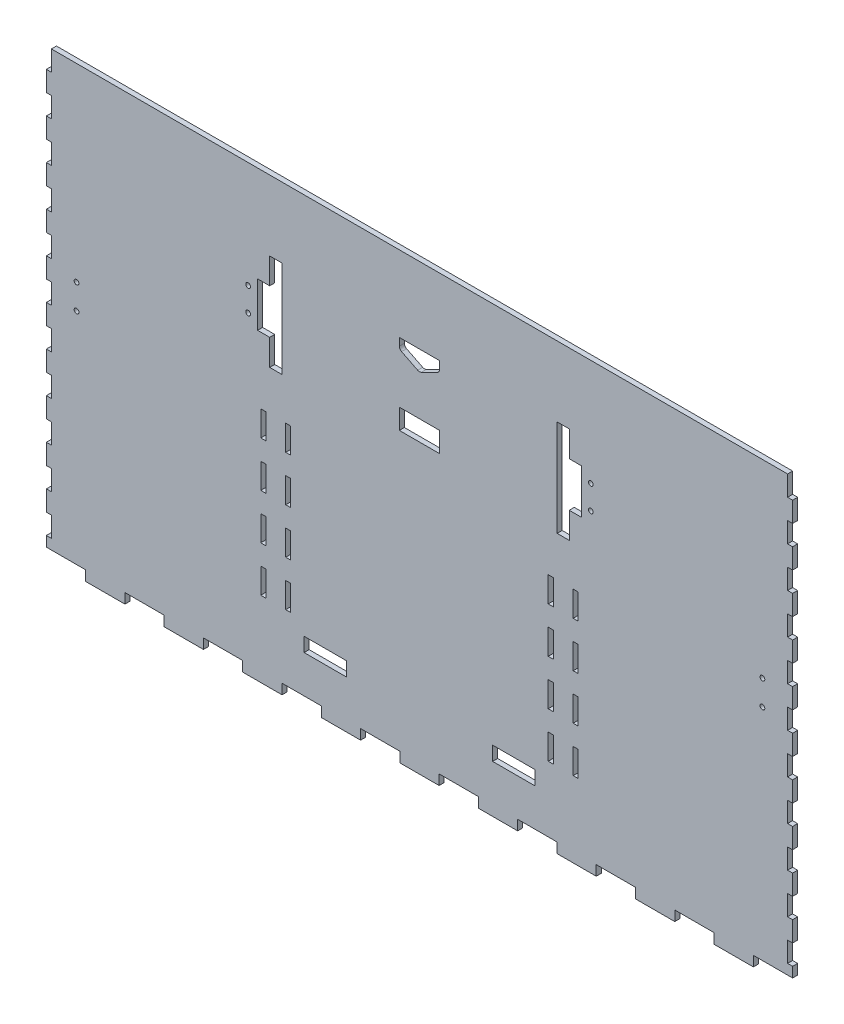
SolidWorks part; units mm, degrees
material "Acrylic (Medium-high impact)"
ref_plane "Front Plane" through (0, 0, 0) normal (0, 0, 1) x (1, 0, 0)
ref_plane "Top Plane" through (0, 0, 0) normal (0, 1, 0) x (1, 0, 0)
ref_plane "Right Plane" through (0, 0, 0) normal (1, 0, 0) x (0, 0, -1)
sketch "Sketch1" plane through (0, 0, 0) normal (0, 1, 0) x (1, 0, 0)
  line L1 (-235.3945, 69.85) -> (235.3945, 69.85)
  line L2 (-235.3945, 69.85) -> (-235.3945, -69.85)
  line L3 (-235.3945, -69.85) -> (235.3945, -69.85)
  line L4 (235.3945, 69.85) -> (235.3945, -69.85)
  point P4 (-235.3945, 0)
  point P6 (0, 69.85)
  dimension "D1" = 139.7
  dimension "D2" = 470.789
extrude "Boss-Extrude1" add sketch "Sketch1" along normal blind 6.35
sketch "Sketch2" plane through (0, 6.35, 0) normal (0, 1, 0) x (1, 0, 0)
  line L0 (235.3945, -69.85) -> (235.3945, 69.85) construction
  line L1 (-235.3945, 69.85) -> (235.3945, 69.85)
  line L2 (-235.3945, 69.85) -> (-235.3945, -69.85)
  line L3 (-235.3945, -69.85) -> (235.3945, -69.85)
  line L4 (235.3945, 69.85) -> (235.3945, -69.85)
  line L5 (-235.3945, -69.85) -> (235.3945, -69.85) construction
  line L7 (-232.2195, 66.675) -> (232.2195, 66.675)
  line L8 (-232.2195, 66.675) -> (-232.2195, -66.675)
  line L9 (-232.2195, -66.675) -> (232.2195, -66.675)
  line L10 (232.2195, 66.675) -> (232.2195, -66.675)
  point P7 (-232.2195, 0)
  point P14 (-235.3945, 0)
  point P15 (0, -66.675)
  point P16 (0, -69.85)
  point P17 (232.2195, 0)
  point P18 (235.3945, 0)
  dimension "D1" = 3.175
  dimension "D2" = 3.175
extrude "Boss-Extrude2" add sketch "Sketch2" along normal blind 299.212
sketch "Sketch3" plane through (0, 0, 69.85) normal (0, 0, 1) x (1, 0, 0)
  line L0 (90.678, 101.6) -> (90.678, 0) construction
  line L1 (-95.6945, 266.954) -> (-85.6615, 266.954)
  line L2 (-232.2195, 6.35) -> (232.2195, 6.35) construction
  line L4 (85.6615, 266.954) -> (85.6615, 6.35)
  line L5 (85.6615, 6.35) -> (95.6945, 6.35)
  line L6 (95.6945, 266.954) -> (95.6945, 6.35)
  line L11 (95.6945, 101.6) -> (78.5495, 101.6) construction
  line L12 (-235.3945, 0) -> (235.3945, 0) construction
  line L13 (75.7555, 88.9) -> (75.7555, 101.6) construction
  line L14 (72.9615, 88.9) -> (78.5495, 88.9)
  line L15 (72.9615, 88.9) -> (72.9615, 71.9667)
  line L16 (72.9615, 71.9667) -> (78.5495, 71.9667)
  line L17 (78.5495, 88.9) -> (78.5495, 71.9667)
  line L18 (72.9615, 42.3333) -> (78.5495, 42.3333)
  line L19 (72.9615, 42.3333) -> (72.9615, 59.2667)
  line L20 (72.9615, 59.2667) -> (78.5495, 59.2667)
  line L21 (78.5495, 42.3333) -> (78.5495, 59.2667)
  line L26 (72.9615, 29.6333) -> (78.5495, 29.6333)
  line L27 (72.9615, 29.6333) -> (72.9615, 12.7)
  line L28 (72.9615, 12.7) -> (78.5495, 12.7)
  line L29 (78.5495, 29.6333) -> (78.5495, 12.7)
  line L30 (75.7555, 59.2667) -> (75.7555, 71.9667) construction
  line L31 (75.7555, 29.6333) -> (75.7555, 42.3333) construction
  line L32 (75.7555, 12.7) -> (75.7555, 0) construction
  line L34 (-95.6945, 266.954) -> (-95.6945, 6.35)
  line L35 (-95.6945, 6.35) -> (-85.6615, 6.35)
  line L36 (-85.6615, 266.954) -> (-85.6615, 6.35)
  line L40 (-85.6615, 101.6) -> (-72.9615, 101.6) construction
  line L41 (-75.7555, 88.9) -> (-75.7555, 101.6) construction
  line L42 (-78.5495, 88.9) -> (-72.9615, 88.9)
  line L43 (-78.5495, 88.9) -> (-78.5495, 71.9667)
  line L44 (-78.5495, 71.9667) -> (-72.9615, 71.9667)
  line L45 (-72.9615, 88.9) -> (-72.9615, 71.9667)
  line L46 (-78.5495, 42.3333) -> (-72.9615, 42.3333)
  line L47 (-78.5495, 42.3333) -> (-78.5495, 59.2667)
  line L48 (-78.5495, 59.2667) -> (-72.9615, 59.2667)
  line L49 (-72.9615, 42.3333) -> (-72.9615, 59.2667)
  line L50 (-78.5495, 29.6333) -> (-72.9615, 29.6333)
  line L51 (-78.5495, 29.6333) -> (-78.5495, 12.7)
  line L52 (-78.5495, 12.7) -> (-72.9615, 12.7)
  line L53 (-72.9615, 29.6333) -> (-72.9615, 12.7)
  line L54 (-75.7555, 59.2667) -> (-75.7555, 71.9667) construction
  line L55 (-75.7555, 29.6333) -> (-75.7555, 42.3333) construction
  line L56 (-75.7555, 12.7) -> (-75.7555, 0) construction
  line L57 (85.6615, 266.954) -> (95.6945, 266.954)
  line L61 (-235.3945, 305.562) -> (-235.3945, 0) construction
  line L62 (235.3945, 305.562) -> (235.3945, 0) construction
  point P5 (90.678, 6.35)
  dimension "D6" = 101.6
  dimension "D8" = 12.7
  dimension "D9" = 5.588
  dimension "D11" = 10.033
  dimension "D13" = 260.604
  dimension "D15" = 12.7
  dimension "D16" = 12.7
  dimension "D17" = 5.588
  dimension "D7" = 12.7
  dimension "D3" = 139.7
  dimension "D4" = 139.7
extrude "Door Slot" cut sketch "Sketch3" against normal blind 12.7
sketch "Sketch4" plane through (0, 0, -66.675) normal (0, 0, 1) x (1, 0, 0)
  line L0 (-235.3945, 305.562) -> (235.3945, 305.562) construction
  line L1 (81.2165, 305.562) -> (84.3915, 305.562)
  line L2 (81.2165, 305.562) -> (81.2165, 6.35)
  line L3 (81.2165, 6.35) -> (84.3915, 6.35)
  line L4 (84.3915, 305.562) -> (84.3915, 6.35)
  line L5 (98.552, 264.2108) -> (98.552, 248.2596) construction
  line L6 (-95.6945, 266.954) -> (-85.6615, 266.954) construction
  line L7 (96.9645, 305.562) -> (100.1395, 305.562)
  line L8 (96.9645, 305.562) -> (96.9645, 6.35)
  line L9 (96.9645, 6.35) -> (100.1395, 6.35)
  line L10 (100.1395, 305.562) -> (100.1395, 6.35)
  line L11 (232.2195, 6.35) -> (-232.2195, 6.35) construction
  line L12 (-95.6945, 266.954) -> (-95.6945, 6.35) construction
  line L13 (84.3915, 305.562) -> (81.2165, 305.562)
  line L14 (84.3915, 305.562) -> (84.3915, 292.862)
  line L15 (84.3915, 292.862) -> (81.2165, 292.862)
  line L16 (81.2165, 305.562) -> (81.2165, 292.862)
  line L17 (84.3915, 276.9108) -> (81.2165, 276.9108)
  line L18 (84.3915, 276.9108) -> (84.3915, 264.2108)
  line L19 (84.3915, 264.2108) -> (81.2165, 264.2108)
  line L20 (81.2165, 276.9108) -> (81.2165, 264.2108)
  line L21 (81.2165, 6.35) -> (84.3915, 6.35)
  line L22 (81.2165, 6.35) -> (81.2165, 19.05)
  line L23 (81.2165, 19.05) -> (84.3915, 19.05)
  line L24 (84.3915, 6.35) -> (84.3915, 19.05)
  line L25 (81.2165, 35.0012) -> (84.3915, 35.0012)
  line L26 (81.2165, 35.0012) -> (81.2165, 47.7012)
  line L27 (81.2165, 47.7012) -> (84.3915, 47.7012)
  line L28 (84.3915, 35.0012) -> (84.3915, 47.7012)
  line L29 (81.2165, 92.3036) -> (84.3915, 92.3036)
  line L30 (81.2165, 92.3036) -> (81.2165, 105.0036)
  line L31 (81.2165, 105.0036) -> (84.3915, 105.0036)
  line L32 (84.3915, 92.3036) -> (84.3915, 105.0036)
  line L33 (81.2165, 149.606) -> (84.3915, 149.606)
  line L34 (81.2165, 149.606) -> (81.2165, 162.306)
  line L35 (81.2165, 162.306) -> (84.3915, 162.306)
  line L36 (84.3915, 149.606) -> (84.3915, 162.306)
  line L37 (81.2165, 178.2572) -> (84.3915, 178.2572)
  line L38 (81.2165, 178.2572) -> (81.2165, 190.9572)
  line L39 (81.2165, 190.9572) -> (84.3915, 190.9572)
  line L40 (84.3915, 178.2572) -> (84.3915, 190.9572)
  line L41 (81.2165, 206.9084) -> (84.3915, 206.9084)
  line L42 (81.2165, 206.9084) -> (81.2165, 219.6084)
  line L43 (81.2165, 219.6084) -> (84.3915, 219.6084)
  line L44 (84.3915, 206.9084) -> (84.3915, 219.6084)
  line L45 (81.2165, 235.5596) -> (84.3915, 235.5596)
  line L46 (81.2165, 235.5596) -> (81.2165, 248.2596)
  line L47 (81.2165, 248.2596) -> (84.3915, 248.2596)
  line L48 (84.3915, 235.5596) -> (84.3915, 248.2596)
  line L49 (84.3915, 133.6548) -> (81.2165, 133.6548)
  line L50 (84.3915, 133.6548) -> (84.3915, 120.9548)
  line L51 (84.3915, 120.9548) -> (81.2165, 120.9548)
  line L52 (81.2165, 133.6548) -> (81.2165, 120.9548)
  line L53 (84.3915, 76.3524) -> (81.2165, 76.3524)
  line L54 (84.3915, 76.3524) -> (84.3915, 63.6524)
  line L55 (84.3915, 63.6524) -> (81.2165, 63.6524)
  line L56 (81.2165, 76.3524) -> (81.2165, 63.6524)
  line L57 (82.804, 305.562) -> (82.804, 292.862) construction
  line L58 (82.804, 292.862) -> (82.804, 276.9108) construction
  line L59 (82.804, 276.9108) -> (82.804, 264.2108) construction
  line L60 (82.804, 248.2596) -> (82.804, 235.5596) construction
  line L61 (82.804, 235.5596) -> (82.804, 219.6084) construction
  line L62 (82.804, 219.6084) -> (82.804, 206.9084) construction
  line L63 (82.804, 206.9084) -> (82.804, 190.9572) construction
  line L64 (82.804, 190.9572) -> (82.804, 178.2572) construction
  line L65 (82.804, 178.2572) -> (82.804, 162.306) construction
  line L66 (82.804, 162.306) -> (82.804, 149.606) construction
  line L67 (82.804, 133.6548) -> (82.804, 120.9548) construction
  line L68 (82.804, 120.9548) -> (82.804, 105.0036) construction
  line L69 (82.804, 105.0036) -> (82.804, 92.3036) construction
  line L70 (82.804, 92.3036) -> (82.804, 76.3524) construction
  line L71 (82.804, 76.3524) -> (82.804, 63.6524) construction
  line L72 (82.804, 63.6524) -> (82.804, 47.7012) construction
  line L73 (82.804, 47.7012) -> (82.804, 35.0012) construction
  line L74 (82.804, 35.0012) -> (82.804, 19.05) construction
  line L75 (82.804, 19.05) -> (82.804, 6.35) construction
  line L76 (82.804, 149.606) -> (82.804, 133.6548) construction
  line L77 (82.804, 264.2108) -> (82.804, 248.2596) construction
  line L78 (90.678, 305.562) -> (90.678, 0) construction
  line L79 (235.3945, 305.562) -> (-235.3945, 305.562) construction
  line L80 (235.3945, 0) -> (-235.3945, 0) construction
  line L81 (90.678, 15.1854) -> (96.9645, 15.1854) construction
  line L82 (90.678, 15.1854) -> (84.3915, 15.1854) construction
  line L83 (98.552, 149.606) -> (98.552, 133.6548) construction
  line L84 (98.552, 19.05) -> (98.552, 6.35) construction
  line L85 (98.552, 35.0012) -> (98.552, 19.05) construction
  line L86 (98.552, 47.7012) -> (98.552, 35.0012) construction
  line L87 (98.552, 63.6524) -> (98.552, 47.7012) construction
  line L88 (98.552, 76.3524) -> (98.552, 63.6524) construction
  line L89 (98.552, 92.3036) -> (98.552, 76.3524) construction
  line L90 (98.552, 105.0036) -> (98.552, 92.3036) construction
  line L91 (98.552, 120.9548) -> (98.552, 105.0036) construction
  line L92 (98.552, 133.6548) -> (98.552, 120.9548) construction
  line L93 (98.552, 162.306) -> (98.552, 149.606) construction
  line L94 (98.552, 178.2572) -> (98.552, 162.306) construction
  line L95 (98.552, 190.9572) -> (98.552, 178.2572) construction
  line L96 (98.552, 206.9084) -> (98.552, 190.9572) construction
  line L97 (98.552, 219.6084) -> (98.552, 206.9084) construction
  line L98 (98.552, 235.5596) -> (98.552, 219.6084) construction
  line L99 (98.552, 248.2596) -> (98.552, 235.5596) construction
  line L100 (98.552, 276.9108) -> (98.552, 264.2108) construction
  line L101 (98.552, 292.862) -> (98.552, 276.9108) construction
  line L102 (98.552, 305.562) -> (98.552, 292.862) construction
  line L103 (100.1395, 76.3524) -> (100.1395, 63.6524)
  line L104 (96.9645, 63.6524) -> (100.1395, 63.6524)
  line L105 (96.9645, 76.3524) -> (96.9645, 63.6524)
  line L106 (96.9645, 76.3524) -> (100.1395, 76.3524)
  line L107 (100.1395, 133.6548) -> (100.1395, 120.9548)
  line L108 (96.9645, 120.9548) -> (100.1395, 120.9548)
  line L109 (96.9645, 133.6548) -> (96.9645, 120.9548)
  line L110 (96.9645, 133.6548) -> (100.1395, 133.6548)
  line L111 (96.9645, 235.5596) -> (96.9645, 248.2596)
  line L112 (100.1395, 248.2596) -> (96.9645, 248.2596)
  line L113 (100.1395, 235.5596) -> (100.1395, 248.2596)
  line L114 (100.1395, 235.5596) -> (96.9645, 235.5596)
  line L115 (96.9645, 206.9084) -> (96.9645, 219.6084)
  line L116 (100.1395, 219.6084) -> (96.9645, 219.6084)
  line L117 (100.1395, 206.9084) -> (100.1395, 219.6084)
  line L118 (100.1395, 206.9084) -> (96.9645, 206.9084)
  line L119 (96.9645, 178.2572) -> (96.9645, 190.9572)
  line L120 (100.1395, 190.9572) -> (96.9645, 190.9572)
  line L121 (100.1395, 178.2572) -> (100.1395, 190.9572)
  line L122 (100.1395, 178.2572) -> (96.9645, 178.2572)
  line L123 (96.9645, 149.606) -> (96.9645, 162.306)
  line L124 (100.1395, 162.306) -> (96.9645, 162.306)
  line L125 (100.1395, 149.606) -> (100.1395, 162.306)
  line L126 (100.1395, 149.606) -> (96.9645, 149.606)
  line L127 (96.9645, 92.3036) -> (96.9645, 105.0036)
  line L128 (100.1395, 105.0036) -> (96.9645, 105.0036)
  line L129 (100.1395, 92.3036) -> (100.1395, 105.0036)
  line L130 (100.1395, 92.3036) -> (96.9645, 92.3036)
  line L131 (96.9645, 35.0012) -> (96.9645, 47.7012)
  line L132 (100.1395, 47.7012) -> (96.9645, 47.7012)
  line L133 (100.1395, 35.0012) -> (100.1395, 47.7012)
  line L134 (100.1395, 35.0012) -> (96.9645, 35.0012)
  line L135 (96.9645, 6.35) -> (96.9645, 19.05)
  line L136 (100.1395, 19.05) -> (96.9645, 19.05)
  line L137 (100.1395, 6.35) -> (100.1395, 19.05)
  line L138 (100.1395, 6.35) -> (96.9645, 6.35)
  line L139 (100.1395, 276.9108) -> (100.1395, 264.2108)
  line L140 (96.9645, 264.2108) -> (100.1395, 264.2108)
  line L141 (96.9645, 276.9108) -> (96.9645, 264.2108)
  line L142 (96.9645, 276.9108) -> (100.1395, 276.9108)
  line L143 (100.1395, 305.562) -> (100.1395, 292.862)
  line L144 (96.9645, 292.862) -> (100.1395, 292.862)
  line L145 (96.9645, 305.562) -> (96.9645, 292.862)
  line L146 (96.9645, 305.562) -> (100.1395, 305.562)
  line L147 (96.9645, 305.562) -> (96.9645, 6.35)
  line L148 (100.1395, 6.35) -> (96.9645, 6.35)
  line L149 (100.1395, 305.562) -> (100.1395, 6.35)
  line L150 (100.1395, 305.562) -> (96.9645, 305.562)
  line L151 (-100.1395, 305.562) -> (-96.9645, 305.562)
  line L152 (-100.1395, 305.562) -> (-100.1395, 6.35)
  line L153 (-100.1395, 6.35) -> (-96.9645, 6.35)
  line L154 (-96.9645, 305.562) -> (-96.9645, 6.35)
  line L155 (-82.804, 264.2108) -> (-82.804, 248.2596) construction
  line L156 (-84.3915, 305.562) -> (-81.2165, 305.562)
  line L157 (-84.3915, 305.562) -> (-84.3915, 6.35)
  line L158 (-84.3915, 6.35) -> (-81.2165, 6.35)
  line L159 (-81.2165, 305.562) -> (-81.2165, 6.35)
  line L160 (-96.9645, 305.562) -> (-100.1395, 305.562)
  line L161 (-96.9645, 305.562) -> (-96.9645, 292.862)
  line L162 (-96.9645, 292.862) -> (-100.1395, 292.862)
  line L163 (-100.1395, 305.562) -> (-100.1395, 292.862)
  line L164 (-96.9645, 276.9108) -> (-100.1395, 276.9108)
  line L165 (-96.9645, 276.9108) -> (-96.9645, 264.2108)
  line L166 (-96.9645, 264.2108) -> (-100.1395, 264.2108)
  line L167 (-100.1395, 276.9108) -> (-100.1395, 264.2108)
  line L168 (-100.1395, 6.35) -> (-96.9645, 6.35)
  line L169 (-100.1395, 6.35) -> (-100.1395, 19.05)
  line L170 (-100.1395, 19.05) -> (-96.9645, 19.05)
  line L171 (-96.9645, 6.35) -> (-96.9645, 19.05)
  line L172 (-100.1395, 35.0012) -> (-96.9645, 35.0012)
  line L173 (-100.1395, 35.0012) -> (-100.1395, 47.7012)
  line L174 (-100.1395, 47.7012) -> (-96.9645, 47.7012)
  line L175 (-96.9645, 35.0012) -> (-96.9645, 47.7012)
  line L176 (-100.1395, 92.3036) -> (-96.9645, 92.3036)
  line L177 (-100.1395, 92.3036) -> (-100.1395, 105.0036)
  line L178 (-100.1395, 105.0036) -> (-96.9645, 105.0036)
  line L179 (-96.9645, 92.3036) -> (-96.9645, 105.0036)
  line L180 (-100.1395, 149.606) -> (-96.9645, 149.606)
  line L181 (-100.1395, 149.606) -> (-100.1395, 162.306)
  line L182 (-100.1395, 162.306) -> (-96.9645, 162.306)
  line L183 (-96.9645, 149.606) -> (-96.9645, 162.306)
  line L184 (-100.1395, 178.2572) -> (-96.9645, 178.2572)
  line L185 (-100.1395, 178.2572) -> (-100.1395, 190.9572)
  line L186 (-100.1395, 190.9572) -> (-96.9645, 190.9572)
  line L187 (-96.9645, 178.2572) -> (-96.9645, 190.9572)
  line L188 (-100.1395, 206.9084) -> (-96.9645, 206.9084)
  line L189 (-100.1395, 206.9084) -> (-100.1395, 219.6084)
  line L190 (-100.1395, 219.6084) -> (-96.9645, 219.6084)
  line L191 (-96.9645, 206.9084) -> (-96.9645, 219.6084)
  line L192 (-100.1395, 235.5596) -> (-96.9645, 235.5596)
  line L193 (-100.1395, 235.5596) -> (-100.1395, 248.2596)
  line L194 (-100.1395, 248.2596) -> (-96.9645, 248.2596)
  line L195 (-96.9645, 235.5596) -> (-96.9645, 248.2596)
  line L196 (-96.9645, 133.6548) -> (-100.1395, 133.6548)
  line L197 (-96.9645, 133.6548) -> (-96.9645, 120.9548)
  line L198 (-96.9645, 120.9548) -> (-100.1395, 120.9548)
  line L199 (-100.1395, 133.6548) -> (-100.1395, 120.9548)
  line L200 (-96.9645, 76.3524) -> (-100.1395, 76.3524)
  line L201 (-96.9645, 76.3524) -> (-96.9645, 63.6524)
  line L202 (-96.9645, 63.6524) -> (-100.1395, 63.6524)
  line L203 (-100.1395, 76.3524) -> (-100.1395, 63.6524)
  line L204 (-98.552, 305.562) -> (-98.552, 292.862) construction
  line L205 (-98.552, 292.862) -> (-98.552, 276.9108) construction
  line L206 (-98.552, 276.9108) -> (-98.552, 264.2108) construction
  line L207 (-98.552, 248.2596) -> (-98.552, 235.5596) construction
  line L208 (-98.552, 235.5596) -> (-98.552, 219.6084) construction
  line L209 (-98.552, 219.6084) -> (-98.552, 206.9084) construction
  line L210 (-98.552, 206.9084) -> (-98.552, 190.9572) construction
  line L211 (-98.552, 190.9572) -> (-98.552, 178.2572) construction
  line L212 (-98.552, 178.2572) -> (-98.552, 162.306) construction
  line L213 (-98.552, 162.306) -> (-98.552, 149.606) construction
  line L214 (-98.552, 133.6548) -> (-98.552, 120.9548) construction
  line L215 (-98.552, 120.9548) -> (-98.552, 105.0036) construction
  line L216 (-98.552, 105.0036) -> (-98.552, 92.3036) construction
  line L217 (-98.552, 92.3036) -> (-98.552, 76.3524) construction
  line L218 (-98.552, 76.3524) -> (-98.552, 63.6524) construction
  line L219 (-98.552, 63.6524) -> (-98.552, 47.7012) construction
  line L220 (-98.552, 47.7012) -> (-98.552, 35.0012) construction
  line L221 (-98.552, 35.0012) -> (-98.552, 19.05) construction
  line L222 (-98.552, 19.05) -> (-98.552, 6.35) construction
  line L223 (-98.552, 149.606) -> (-98.552, 133.6548) construction
  line L224 (-98.552, 264.2108) -> (-98.552, 248.2596) construction
  line L225 (-90.678, 305.562) -> (-90.678, 0) construction
  line L226 (-90.678, 341.727) -> (-84.3915, 341.727) construction
  line L227 (-90.678, 341.727) -> (-96.9645, 341.727) construction
  line L228 (-82.804, 149.606) -> (-82.804, 133.6548) construction
  line L229 (-82.804, 19.05) -> (-82.804, 6.35) construction
  line L230 (-82.804, 35.0012) -> (-82.804, 19.05) construction
  line L231 (-82.804, 47.7012) -> (-82.804, 35.0012) construction
  line L232 (-82.804, 63.6524) -> (-82.804, 47.7012) construction
  line L233 (-82.804, 76.3524) -> (-82.804, 63.6524) construction
  line L234 (-82.804, 92.3036) -> (-82.804, 76.3524) construction
  line L235 (-82.804, 105.0036) -> (-82.804, 92.3036) construction
  line L236 (-82.804, 120.9548) -> (-82.804, 105.0036) construction
  line L237 (-82.804, 133.6548) -> (-82.804, 120.9548) construction
  line L238 (-82.804, 162.306) -> (-82.804, 149.606) construction
  line L239 (-82.804, 178.2572) -> (-82.804, 162.306) construction
  line L240 (-82.804, 190.9572) -> (-82.804, 178.2572) construction
  line L241 (-82.804, 206.9084) -> (-82.804, 190.9572) construction
  line L242 (-82.804, 219.6084) -> (-82.804, 206.9084) construction
  line L243 (-82.804, 235.5596) -> (-82.804, 219.6084) construction
  line L244 (-82.804, 248.2596) -> (-82.804, 235.5596) construction
  line L245 (-82.804, 276.9108) -> (-82.804, 264.2108) construction
  line L246 (-82.804, 292.862) -> (-82.804, 276.9108) construction
  line L247 (-82.804, 305.562) -> (-82.804, 292.862) construction
  line L248 (-81.2165, 76.3524) -> (-81.2165, 63.6524)
  line L249 (-84.3915, 63.6524) -> (-81.2165, 63.6524)
  line L250 (-84.3915, 76.3524) -> (-84.3915, 63.6524)
  line L251 (-84.3915, 76.3524) -> (-81.2165, 76.3524)
  line L252 (-81.2165, 133.6548) -> (-81.2165, 120.9548)
  line L253 (-84.3915, 120.9548) -> (-81.2165, 120.9548)
  line L254 (-84.3915, 133.6548) -> (-84.3915, 120.9548)
  line L255 (-84.3915, 133.6548) -> (-81.2165, 133.6548)
  line L256 (-84.3915, 235.5596) -> (-84.3915, 248.2596)
  line L257 (-81.2165, 248.2596) -> (-84.3915, 248.2596)
  line L258 (-81.2165, 235.5596) -> (-81.2165, 248.2596)
  line L259 (-81.2165, 235.5596) -> (-84.3915, 235.5596)
  line L260 (-84.3915, 206.9084) -> (-84.3915, 219.6084)
  line L261 (-81.2165, 219.6084) -> (-84.3915, 219.6084)
  line L262 (-81.2165, 206.9084) -> (-81.2165, 219.6084)
  line L263 (-81.2165, 206.9084) -> (-84.3915, 206.9084)
  line L264 (-84.3915, 178.2572) -> (-84.3915, 190.9572)
  line L265 (-81.2165, 190.9572) -> (-84.3915, 190.9572)
  line L266 (-81.2165, 178.2572) -> (-81.2165, 190.9572)
  line L267 (-81.2165, 178.2572) -> (-84.3915, 178.2572)
  line L268 (-84.3915, 149.606) -> (-84.3915, 162.306)
  line L269 (-81.2165, 162.306) -> (-84.3915, 162.306)
  line L270 (-81.2165, 149.606) -> (-81.2165, 162.306)
  line L271 (-81.2165, 149.606) -> (-84.3915, 149.606)
  line L272 (-84.3915, 92.3036) -> (-84.3915, 105.0036)
  line L273 (-81.2165, 105.0036) -> (-84.3915, 105.0036)
  line L274 (-81.2165, 92.3036) -> (-81.2165, 105.0036)
  line L275 (-81.2165, 92.3036) -> (-84.3915, 92.3036)
  line L276 (-84.3915, 35.0012) -> (-84.3915, 47.7012)
  line L277 (-81.2165, 47.7012) -> (-84.3915, 47.7012)
  line L278 (-81.2165, 35.0012) -> (-81.2165, 47.7012)
  line L279 (-81.2165, 35.0012) -> (-84.3915, 35.0012)
  line L280 (-84.3915, 6.35) -> (-84.3915, 19.05)
  line L281 (-81.2165, 19.05) -> (-84.3915, 19.05)
  line L282 (-81.2165, 6.35) -> (-81.2165, 19.05)
  line L283 (-81.2165, 6.35) -> (-84.3915, 6.35)
  line L284 (-81.2165, 276.9108) -> (-81.2165, 264.2108)
  line L285 (-84.3915, 264.2108) -> (-81.2165, 264.2108)
  line L286 (-84.3915, 276.9108) -> (-84.3915, 264.2108)
  line L287 (-84.3915, 276.9108) -> (-81.2165, 276.9108)
  line L288 (-81.2165, 305.562) -> (-81.2165, 292.862)
  line L289 (-84.3915, 292.862) -> (-81.2165, 292.862)
  line L290 (-84.3915, 305.562) -> (-84.3915, 292.862)
  line L291 (-84.3915, 305.562) -> (-81.2165, 305.562)
  line L292 (-84.3915, 305.562) -> (-84.3915, 6.35)
  line L293 (-81.2165, 6.35) -> (-84.3915, 6.35)
  line L294 (-81.2165, 305.562) -> (-81.2165, 6.35)
  line L295 (-81.2165, 305.562) -> (-84.3915, 305.562)
  line L296 (-235.3945, 0) -> (235.3945, 0) construction
  line L301 (85.6615, 266.954) -> (95.6945, 266.954) construction
  line L302 (85.6615, 266.954) -> (85.6615, 6.35) construction
  point P290 (-90.678, 266.954)
  point P297 (90.678, 266.954)
  dimension "D1" = 3.175
  dimension "D2" = 12.7
  dimension "D3" = 3.175
  dimension "D4" = 12.7
  dimension "D5" = 1.27
  dimension "D6" = 1.27
extrude "Door Guide Holes" cut sketch "Sketch4" against normal up to next contours L154 L202 L152 L174 | L277 L159 L249 L157 | L200 L154 L176 L152 | L159 L275 L157 L251 | L273 L159 L253 L157 | L154 L198 L152 L178 | L196 L154 L180 L152 | L159 L271 L157 L255 | L49 L4 L33 L2 | L4 L51 L2 L31 | L10 L126 L8 L110 | L128 L10 L108 L8 | L53 L4 L29 L2 | L10 L130 L8 L106 | L132 L10 L104 L8 | L4 L55 L2 L27 region at (82.804, 141.6304, -66.675) region at (82.804, 112.9792, -66.675) region at (82.804, 84.328, -66.675) region at (82.804, 55.6768, -66.675) region at (98.552, 141.6304, -66.675) region at (98.552, 112.9792, -66.675) region at (98.552, 84.328, -66.675) region at (98.552, 55.6768, -66.675) region at (-98.552, 141.6304, -66.675) region at (-98.552, 112.9792, -66.675) region at (-98.552, 84.328, -66.675) region at (-98.552, 55.6768, -66.675) region at (-82.804, 141.6304, -66.675) region at (-82.804, 112.9792, -66.675) region at (-82.804, 84.328, -66.675) region at (-82.804, 55.6768, -66.675)
sketch "Lever Holes" plane through (0, 0, -69.85) normal (0, 0, 1) x (1, 0, 0)
  line L0 (-72.8015, 38.955) -> (-46.1315, 38.955)
  line L1 (-72.8015, 38.955) -> (-72.8015, 30.065)
  line L2 (-72.8015, 30.065) -> (-46.1315, 30.065)
  line L3 (-46.1315, 38.955) -> (-46.1315, 30.065)
  line L4 (-72.7165, 16.35) -> (-68.7165, 16.35)
  line L5 (-72.7165, 16.35) -> (-72.7165, 10)
  line L6 (-72.7165, 10) -> (-68.7165, 10)
  line L7 (-68.7165, 16.35) -> (-68.7165, 10)
  line L8 (-26.7165, 16.35) -> (-22.7165, 16.35)
  line L9 (-26.7165, 16.35) -> (-26.7165, 10)
  line L10 (-26.7165, 10) -> (-22.7165, 10)
  line L11 (-22.7165, 16.35) -> (-22.7165, 10)
  line L12 (-68.7165, 13.175) -> (-26.7165, 13.175) construction
  line L13 (95.6945, 6.35) -> (95.6945, 266.954) construction
  line L14 (95.6945, 6.35) -> (232.2195, 6.35) construction
  line L15 (232.2195, 6.35) -> (-232.2195, 6.35) construction
  line L16 (216.3445, 160.655) -> (216.3445, 144.907) construction
  line L17 (235.3945, 305.562) -> (235.3945, 0) construction
  line L18 (0, -1.7463) -> (0, 1.7463) construction
  line L19 (95.6945, 154.6735) -> (-95.6945, 154.6735) construction
  line L20 (-95.6945, 266.954) -> (-95.6945, 6.35) construction
  line L21 (0, 171.6172) -> (0, 142.0428) construction
  line L22 (26.7165, 16.35) -> (26.7165, 10)
  line L23 (26.7165, 10) -> (22.7165, 10)
  line L24 (22.7165, 16.35) -> (22.7165, 10)
  line L25 (26.7165, 16.35) -> (22.7165, 16.35)
  line L26 (72.8015, 38.955) -> (72.8015, 30.065)
  line L27 (72.8015, 30.065) -> (46.1315, 30.065)
  line L28 (46.1315, 38.955) -> (46.1315, 30.065)
  line L29 (72.8015, 38.955) -> (46.1315, 38.955)
  line L30 (72.7165, 16.35) -> (72.7165, 10)
  line L31 (72.7165, 10) -> (68.7165, 10)
  line L32 (68.7165, 16.35) -> (68.7165, 10)
  line L33 (72.7165, 16.35) -> (68.7165, 16.35)
  line L34 (81.2165, 305.562) -> (81.2165, 6.35) construction
  line L35 (-81.2165, 47.7012) -> (-81.2165, 63.6524) construction
  circle A0 centre (216.3445, 160.655) radius 1.5
  circle A1 centre (216.3445, 144.907) radius 1.5
  circle A2 centre (-216.3445, 160.655) radius 1.5
  circle A3 centre (-216.3445, 144.907) radius 1.5
  point P13 (-59.4665, 38.955)
  point P31 (216.3445, 152.781)
  point P32 (235.3945, 152.781)
  dimension "D10" = 3
  dimension "D1" = 26.67
  dimension "D2" = 8.89
  dimension "D3" = 4
  dimension "D4" = 6.35
  dimension "D5" = 42
  dimension "D6" = 23.715
  dimension "D7" = 10
  dimension "D8" = 8.5
  dimension "D9" = 21.75
  dimension "D11" = 15.748
  dimension "D12" = 19.05
extrude "LeverHole Cut" cut sketch "Lever Holes" along normal up to next contours L0 L3 L2 L1 | L29 L26 L27 L28 region at (-59.4665, 34.51, -69.85) region at (59.4665, 34.51, -69.85)
extrude "Lbracket Thru Holes" cut sketch "Lever Holes<2>" along normal through all contours A2 | A3 | A0 | A1 | A2 | A3 | A0 | A1 region at (216.3445, 160.655, -69.85) region at (216.3445, 144.907, -69.85) region at (-216.3445, 160.655, -69.85) region at (-216.3445, 144.907, -69.85)
sketch "Lever Holes<2>" plane through (0, 0, -69.85) normal (0, 0, 1) x (1, 0, 0) same geometry as "Lever Holes"
sketch "Sketch8" plane through (-235.3945, 0, 0) normal (-1, 0, 0) x (0, 0, 1)
  line L0 (-69.85, 0) -> (69.85, 0) construction
  circle A0 centre (0, 11.43) radius 3.175
  point P6 (0, 0)
  dimension "D1" = 6.35
  dimension "D2" = 11.43
extrude "Tether Hole" cut sketch "Sketch8" against normal through all
sketch "Sketch16" plane through (0, 0, 69.85) normal (0, 0, 1) x (1, 0, 0)
  line L1 (63.246, 280.162) -> (118.11, 280.162)
  line L2 (63.246, 280.162) -> (63.246, 268.732)
  line L4 (118.11, 280.162) -> (118.11, 268.732)
  line L6 (53.721, 268.732) -> (63.246, 268.732)
  line L8 (63.246, 268.732) -> (63.246, 280.162)
  line L9 (63.246, 280.162) -> (53.721, 280.162)
  line L10 (53.721, 268.732) -> (53.721, 280.162)
  line L11 (118.11, 268.732) -> (127.635, 268.732)
  line L12 (118.11, 268.732) -> (118.11, 280.162)
  line L13 (118.11, 280.162) -> (127.635, 280.162)
  line L14 (127.635, 268.732) -> (127.635, 280.162)
  line L15 (-235.3945, 305.562) -> (-235.3945, 0) construction
  line L16 (0, -1.7463) -> (0, 1.7463) construction
  line L17 (-118.11, 280.162) -> (-127.635, 280.162)
  line L19 (-127.635, 268.732) -> (-127.635, 280.162)
  line L28 (235.3945, 305.562) -> (-235.3945, 305.562)
  line L29 (-118.11, 268.732) -> (-127.635, 268.732)
  line L30 (-118.11, 268.732) -> (-118.11, 280.162)
  line L31 (-63.246, 280.162) -> (-63.246, 268.732)
  line L32 (-63.246, 280.162) -> (-53.721, 280.162)
  line L33 (-53.721, 268.732) -> (-53.721, 280.162)
  line L34 (-53.721, 268.732) -> (-63.246, 268.732)
  line L35 (235.3945, 305.562) -> (235.3945, 280.162)
  line L36 (235.3945, 280.162) -> (-235.3945, 280.162)
  line L37 (-235.3945, 305.562) -> (-235.3945, 280.162)
  line L38 (95.6945, 6.35) -> (232.2195, 6.35) construction
  line L39 (90.678, 266.954) -> (90.678, 280.162) construction
  line L40 (95.6945, 266.954) -> (85.6615, 266.954) construction
  line M71 (235.3945, 0) -> (235.3945, 305.562)
  line M72 (235.3945, 305.562) -> (-235.3945, 305.562)
  line M73 (-235.3945, 305.562) -> (-235.3945, 0)
  dimension "D1" = 54.864
  dimension "D2" = 273.812
  dimension "D3" = 9.525
  dimension "D4" = 11.43
extrude "HeightReduction" cut sketch "Sketch16" against normal up to next contours L36 L17 L32 L9 L1 L13 M71 M72 M73 region at (0, 292.862, 69.85)
sketch "Bottom" plane through (0, 0, 0) normal (0, -1, 0) x (1, 0, 0)
  line L1 (-235.3945, 69.85) -> (-210.6161, 69.85)
  line L2 (-235.3945, 69.85) -> (-235.3945, 66.675)
  line L3 (-235.3945, 66.675) -> (-210.6161, 66.675)
  line L4 (-210.6161, 69.85) -> (-210.6161, 66.675)
  line L5 (-210.6161, 69.85) -> (-185.8378, 69.85)
  line L6 (-210.6161, 69.85) -> (-210.6161, 66.675)
  line L7 (-210.6161, 66.675) -> (-185.8378, 66.675)
  line L8 (-185.8378, 69.85) -> (-185.8378, 66.675)
  line L9 (-185.8378, 69.85) -> (-161.0594, 69.85)
  line L10 (-185.8378, 69.85) -> (-185.8378, 66.675)
  line L11 (-185.8378, 66.675) -> (-161.0594, 66.675)
  line L12 (-161.0594, 69.85) -> (-161.0594, 66.675)
  line L13 (-161.0594, 69.85) -> (-136.281, 69.85)
  line L14 (-161.0594, 69.85) -> (-161.0594, 66.675)
  line L15 (-161.0594, 66.675) -> (-136.281, 66.675)
  line L16 (-136.281, 69.85) -> (-136.281, 66.675)
  line L17 (-235.3945, 69.85) -> (235.3945, 69.85) construction
  line L18 (232.2195, -66.675) -> (-232.2195, -66.675) construction
  line L19 (-136.281, 69.85) -> (-111.5027, 69.85)
  line L20 (-136.281, 69.85) -> (-136.281, 66.675)
  line L21 (-136.281, 66.675) -> (-111.5027, 66.675)
  line L22 (-111.5027, 69.85) -> (-111.5027, 66.675)
  line L23 (-111.5027, 69.85) -> (-86.7243, 69.85)
  line L24 (-111.5027, 69.85) -> (-111.5027, 66.675)
  line L25 (-111.5027, 66.675) -> (-86.7243, 66.675)
  line L26 (-86.7243, 69.85) -> (-86.7243, 66.675)
  line L27 (-86.7243, 69.85) -> (-61.9459, 69.85)
  line L28 (-86.7243, 69.85) -> (-86.7243, 66.675)
  line L29 (-86.7243, 66.675) -> (-61.9459, 66.675)
  line L30 (-61.9459, 69.85) -> (-61.9459, 66.675)
  line L31 (-61.9459, 69.85) -> (-37.1676, 69.85)
  line L32 (-61.9459, 69.85) -> (-61.9459, 66.675)
  line L33 (-61.9459, 66.675) -> (-37.1676, 66.675)
  line L34 (-37.1676, 69.85) -> (-37.1676, 66.675)
  line L36 (-37.1676, 69.85) -> (-12.3892, 69.85)
  line L37 (-37.1676, 69.85) -> (-37.1676, 66.675)
  line L38 (-37.1676, 66.675) -> (-12.3892, 66.675)
  line L39 (-12.3892, 69.85) -> (-12.3892, 66.675)
  line L40 (-12.3892, 69.85) -> (12.3892, 69.85)
  line L41 (-12.3892, 69.85) -> (-12.3892, 66.675)
  line L42 (-12.3892, 66.675) -> (12.3892, 66.675)
  line L43 (12.3892, 69.85) -> (12.3892, 66.675)
  line L44 (12.3892, 69.85) -> (37.1676, 69.85)
  line L45 (12.3892, 69.85) -> (12.3892, 66.675)
  line L46 (12.3892, 66.675) -> (37.1676, 66.675)
  line L47 (37.1676, 69.85) -> (37.1676, 66.675)
  line L48 (37.1676, 69.85) -> (61.9459, 69.85)
  line L49 (37.1676, 69.85) -> (37.1676, 66.675)
  line L50 (37.1676, 66.675) -> (61.9459, 66.675)
  line L51 (61.9459, 69.85) -> (61.9459, 66.675)
  line L52 (61.9459, 69.85) -> (86.7243, 69.85)
  line L53 (61.9459, 69.85) -> (61.9459, 66.675)
  line L54 (61.9459, 66.675) -> (86.7243, 66.675)
  line L55 (86.7243, 69.85) -> (86.7243, 66.675)
  line L56 (86.7243, 69.85) -> (111.5027, 69.85)
  line L57 (86.7243, 69.85) -> (86.7243, 66.675)
  line L58 (86.7243, 66.675) -> (111.5027, 66.675)
  line L59 (111.5027, 69.85) -> (111.5027, 66.675)
  line L60 (111.5027, 69.85) -> (136.281, 69.85)
  line L61 (111.5027, 69.85) -> (111.5027, 66.675)
  line L62 (111.5027, 66.675) -> (136.281, 66.675)
  line L63 (136.281, 69.85) -> (136.281, 66.675)
  line L64 (136.281, 69.85) -> (161.0594, 69.85)
  line L65 (136.281, 69.85) -> (136.281, 66.675)
  line L66 (136.281, 66.675) -> (161.0594, 66.675)
  line L67 (161.0594, 69.85) -> (161.0594, 66.675)
  line L68 (161.0594, 69.85) -> (185.8378, 69.85)
  line L69 (161.0594, 69.85) -> (161.0594, 66.675)
  line L70 (161.0594, 66.675) -> (185.8378, 66.675)
  line L71 (185.8378, 69.85) -> (185.8378, 66.675)
  line L72 (185.8378, 69.85) -> (210.6161, 69.85)
  line L73 (185.8378, 69.85) -> (185.8378, 66.675)
  line L74 (185.8378, 66.675) -> (210.6161, 66.675)
  line L75 (210.6161, 69.85) -> (210.6161, 66.675)
  line L76 (-232.2195, -66.675) -> (-232.2195, 66.675) construction
  line L77 (-235.3945, 69.85) -> (-232.2195, 69.85)
  line L78 (-235.3945, 69.85) -> (-235.3945, 57.15)
  line L79 (-235.3945, 57.15) -> (-232.2195, 57.15)
  line L80 (-232.2195, 69.85) -> (-232.2195, 57.15)
  line L82 (-235.3945, 57.15) -> (-232.2195, 57.15)
  line L83 (-235.3945, 57.15) -> (-235.3945, 44.45)
  line L84 (-235.3945, 44.45) -> (-232.2195, 44.45)
  line L85 (-232.2195, 57.15) -> (-232.2195, 44.45)
  line L86 (-235.3945, 44.45) -> (-232.2195, 44.45)
  line L87 (-235.3945, 44.45) -> (-235.3945, 31.75)
  line L88 (-235.3945, 31.75) -> (-232.2195, 31.75)
  line L89 (-232.2195, 44.45) -> (-232.2195, 31.75)
  line L90 (-235.3945, 31.75) -> (-232.2195, 31.75)
  line L91 (-235.3945, 31.75) -> (-235.3945, 19.05)
  line L92 (-235.3945, 19.05) -> (-232.2195, 19.05)
  line L93 (-232.2195, 31.75) -> (-232.2195, 19.05)
  line L94 (-235.3945, 19.05) -> (-232.2195, 19.05)
  line L95 (-235.3945, 19.05) -> (-235.3945, 6.35)
  line L96 (-235.3945, 6.35) -> (-232.2195, 6.35)
  line L97 (-232.2195, 19.05) -> (-232.2195, 6.35)
  line L98 (-235.3945, 6.35) -> (-232.2195, 6.35)
  line L99 (-235.3945, 6.35) -> (-235.3945, -6.35)
  line L100 (-235.3945, -6.35) -> (-232.2195, -6.35)
  line L101 (-232.2195, 6.35) -> (-232.2195, -6.35)
  line L102 (-235.3945, -6.35) -> (-232.2195, -6.35)
  line L103 (-235.3945, -6.35) -> (-235.3945, -19.05)
  line L104 (-235.3945, -19.05) -> (-232.2195, -19.05)
  line L105 (-232.2195, -6.35) -> (-232.2195, -19.05)
  line L106 (-235.3945, -19.05) -> (-232.2195, -19.05)
  line L107 (-235.3945, -19.05) -> (-235.3945, -31.75)
  line L108 (-235.3945, -31.75) -> (-232.2195, -31.75)
  line L109 (-232.2195, -19.05) -> (-232.2195, -31.75)
  line L110 (-235.3945, -31.75) -> (-232.2195, -31.75)
  line L111 (-235.3945, -31.75) -> (-235.3945, -44.45)
  line L112 (-235.3945, -44.45) -> (-232.2195, -44.45)
  line L113 (-232.2195, -31.75) -> (-232.2195, -44.45)
  line L114 (-235.3945, -44.45) -> (-232.2195, -44.45)
  line L115 (-235.3945, -44.45) -> (-235.3945, -57.15)
  line L116 (-235.3945, -57.15) -> (-232.2195, -57.15)
  line L117 (-232.2195, -44.45) -> (-232.2195, -57.15)
  line L118 (235.3945, 69.85) -> (235.3945, -69.85) construction
  line L119 (210.6161, 69.85) -> (235.3945, 69.85)
  line L120 (210.6161, 69.85) -> (210.6161, 66.675)
  line L121 (210.6161, 66.675) -> (235.3945, 66.675)
  line L122 (235.3945, 69.85) -> (235.3945, 66.675)
  line L123 (235.3945, -69.85) -> (-235.3945, -69.85) construction
  line L124 (-235.3945, -57.15) -> (-232.2195, -57.15)
  line L125 (-235.3945, -57.15) -> (-235.3945, -69.85)
  line L126 (-235.3945, -69.85) -> (-232.2195, -69.85)
  line L127 (-232.2195, -57.15) -> (-232.2195, -69.85)
  line L128 (154.0891, 0) -> (-154.0891, 0) construction
  line L129 (235.3945, -69.85) -> (235.3945, -66.675)
  line L130 (210.6161, -66.675) -> (235.3945, -66.675)
  line L131 (210.6161, -69.85) -> (235.3945, -69.85)
  line L132 (210.6161, -69.85) -> (210.6161, -66.675)
  line L133 (185.8378, -66.675) -> (210.6161, -66.675)
  line L134 (185.8378, -69.85) -> (210.6161, -69.85)
  line L135 (185.8378, -69.85) -> (185.8378, -66.675)
  line L136 (161.0594, -66.675) -> (185.8378, -66.675)
  line L137 (161.0594, -69.85) -> (185.8378, -69.85)
  line L138 (161.0594, -69.85) -> (161.0594, -66.675)
  line L139 (136.281, -66.675) -> (161.0594, -66.675)
  line L140 (136.281, -69.85) -> (161.0594, -69.85)
  line L141 (136.281, -69.85) -> (136.281, -66.675)
  line L142 (111.5027, -66.675) -> (136.281, -66.675)
  line L143 (111.5027, -69.85) -> (136.281, -69.85)
  line L144 (86.7243, -66.675) -> (111.5027, -66.675)
  line L145 (111.5027, -69.85) -> (111.5027, -66.675)
  line L146 (86.7243, -69.85) -> (111.5027, -69.85)
  line L147 (86.7243, -69.85) -> (86.7243, -66.675)
  line L148 (61.9459, -66.675) -> (86.7243, -66.675)
  line L149 (61.9459, -69.85) -> (86.7243, -69.85)
  line L150 (61.9459, -69.85) -> (61.9459, -66.675)
  line L151 (37.1676, -66.675) -> (61.9459, -66.675)
  line L152 (37.1676, -69.85) -> (61.9459, -69.85)
  line L153 (37.1676, -69.85) -> (37.1676, -66.675)
  line L154 (12.3892, -69.85) -> (37.1676, -69.85)
  line L155 (12.3892, -66.675) -> (37.1676, -66.675)
  line L156 (12.3892, -69.85) -> (12.3892, -66.675)
  line L157 (-12.3892, -66.675) -> (12.3892, -66.675)
  line L158 (-12.3892, -69.85) -> (12.3892, -69.85)
  line L159 (-37.1676, -66.675) -> (-12.3892, -66.675)
  line L160 (-12.3892, -69.85) -> (-12.3892, -66.675)
  line L161 (-37.1676, -69.85) -> (-12.3892, -69.85)
  line L162 (-37.1676, -69.85) -> (-37.1676, -66.675)
  line L163 (-61.9459, -66.675) -> (-37.1676, -66.675)
  line L164 (-61.9459, -69.85) -> (-37.1676, -69.85)
  line L165 (-61.9459, -69.85) -> (-61.9459, -66.675)
  line L166 (-86.7243, -66.675) -> (-61.9459, -66.675)
  line L167 (-86.7243, -69.85) -> (-61.9459, -69.85)
  line L168 (-86.7243, -69.85) -> (-86.7243, -66.675)
  line L169 (-111.5027, -69.85) -> (-86.7243, -69.85)
  line L170 (-111.5027, -66.675) -> (-86.7243, -66.675)
  line L171 (-136.281, -66.675) -> (-111.5027, -66.675)
  line L172 (-111.5027, -69.85) -> (-111.5027, -66.675)
  line L173 (-136.281, -69.85) -> (-111.5027, -69.85)
  line L174 (-161.0594, -69.85) -> (-136.281, -69.85)
  line L175 (-161.0594, -66.675) -> (-136.281, -66.675)
  line L176 (-136.281, -69.85) -> (-136.281, -66.675)
  line L177 (-185.8378, -69.85) -> (-185.8378, -66.675)
  line L178 (-185.8378, -69.85) -> (-161.0594, -69.85)
  line L179 (-161.0594, -69.85) -> (-161.0594, -66.675)
  line L180 (-185.8378, -66.675) -> (-161.0594, -66.675)
  line L181 (-210.6161, -66.675) -> (-185.8378, -66.675)
  line L182 (-210.6161, -69.85) -> (-185.8378, -69.85)
  line L183 (-210.6161, -69.85) -> (-210.6161, -66.675)
  line L184 (-235.3945, -69.85) -> (-210.6161, -69.85)
  line L185 (-235.3945, -69.85) -> (-235.3945, -66.675)
  line L186 (-235.3945, -66.675) -> (-210.6161, -66.675)
  line L187 (0, -1.7463) -> (0, 1.7463) construction
  line L188 (235.3945, -69.85) -> (232.2195, -69.85)
  line L189 (232.2195, -57.15) -> (232.2195, -69.85)
  line L190 (235.3945, -57.15) -> (235.3945, -69.85)
  line L191 (235.3945, -57.15) -> (232.2195, -57.15)
  line L192 (232.2195, -44.45) -> (232.2195, -57.15)
  line L193 (235.3945, -44.45) -> (235.3945, -57.15)
  line L194 (235.3945, -44.45) -> (232.2195, -44.45)
  line L195 (232.2195, -31.75) -> (232.2195, -44.45)
  line L196 (235.3945, -31.75) -> (235.3945, -44.45)
  line L197 (235.3945, -31.75) -> (232.2195, -31.75)
  line L198 (235.3945, -19.05) -> (235.3945, -31.75)
  line L199 (232.2195, -19.05) -> (232.2195, -31.75)
  line L200 (232.2195, -6.35) -> (232.2195, -19.05)
  line L201 (235.3945, -6.35) -> (235.3945, -19.05)
  line L202 (235.3945, -19.05) -> (232.2195, -19.05)
  line L203 (235.3945, -6.35) -> (232.2195, -6.35)
  line L204 (232.2195, 6.35) -> (232.2195, -6.35)
  line L205 (235.3945, 6.35) -> (235.3945, -6.35)
  line L206 (235.3945, 6.35) -> (232.2195, 6.35)
  line L207 (232.2195, 19.05) -> (232.2195, 6.35)
  line L208 (235.3945, 19.05) -> (235.3945, 6.35)
  line L209 (235.3945, 19.05) -> (232.2195, 19.05)
  line L210 (235.3945, 31.75) -> (232.2195, 31.75)
  line L211 (235.3945, 44.45) -> (232.2195, 44.45)
  line L212 (235.3945, 57.15) -> (232.2195, 57.15)
  line L213 (232.2195, 31.75) -> (232.2195, 19.05)
  line L214 (235.3945, 31.75) -> (235.3945, 19.05)
  line L215 (232.2195, 44.45) -> (232.2195, 31.75)
  line L216 (235.3945, 44.45) -> (235.3945, 31.75)
  line L217 (232.2195, 57.15) -> (232.2195, 44.45)
  line L218 (235.3945, 57.15) -> (235.3945, 44.45)
  line L219 (232.2195, 69.85) -> (232.2195, 57.15)
  line L220 (235.3945, 69.85) -> (235.3945, 57.15)
sketch "Front/Back" plane through (0, 0, 69.85) normal (0, 0, 1) x (1, 0, 0)
  line L0 (-232.2195, 6.35) -> (-95.6945, 6.35) construction
  line L1 (-235.3945, 0) -> (-210.6161, 0)
  line L2 (-235.3945, 0) -> (-235.3945, 6.35)
  line L3 (-235.3945, 6.35) -> (-210.6161, 6.35)
  line L4 (-210.6161, 0) -> (-210.6161, 6.35)
  line L5 (-235.3945, 0) -> (235.3945, 0) construction
  line L6 (-185.8378, 0) -> (-161.0594, 0) construction
  line L7 (-210.6161, 6.35) -> (-185.8378, 6.35)
  line L8 (-210.6161, 6.35) -> (-210.6161, 0)
  line L9 (-210.6161, 0) -> (-185.8378, 0)
  line L10 (-185.8378, 6.35) -> (-185.8378, 0)
  line L11 (-136.281, 0) -> (-111.5027, 0) construction
  line L12 (-185.8378, 6.35) -> (-161.0594, 6.35)
  line L13 (-185.8378, 6.35) -> (-185.8378, 0)
  line L14 (-185.8378, 0) -> (-161.0594, 0)
  line L15 (-161.0594, 6.35) -> (-161.0594, 0)
  line L16 (-161.0594, 6.35) -> (-136.281, 6.35)
  line L17 (-161.0594, 6.35) -> (-161.0594, 0)
  line L18 (-161.0594, 0) -> (-136.281, 0)
  line L19 (-136.281, 6.35) -> (-136.281, 0)
  line L20 (-111.5027, 0) -> (-86.7243, 0) construction
  line L21 (-136.281, 6.35) -> (-111.5027, 6.35)
  line L22 (-136.281, 6.35) -> (-136.281, 0)
  line L23 (-136.281, 0) -> (-111.5027, 0)
  line L24 (-111.5027, 6.35) -> (-111.5027, 0)
  line L25 (-111.5027, 6.35) -> (-86.7243, 6.35)
  line L26 (-111.5027, 6.35) -> (-111.5027, 0)
  line L27 (-111.5027, 0) -> (-86.7243, 0)
  line L28 (-86.7243, 6.35) -> (-86.7243, 0)
  line L29 (-86.7243, 0) -> (-61.9459, 0) construction
  line L30 (-86.7243, 6.35) -> (-61.9459, 6.35)
  line L31 (-86.7243, 6.35) -> (-86.7243, 0)
  line L32 (-86.7243, 0) -> (-61.9459, 0)
  line L33 (-61.9459, 6.35) -> (-61.9459, 0)
  line L34 (-37.1676, 0) -> (-12.3892, 0) construction
  line L35 (-61.9459, 6.35) -> (-37.1676, 6.35)
  line L36 (-61.9459, 6.35) -> (-61.9459, 0)
  line L37 (-61.9459, 0) -> (-37.1676, 0)
  line L38 (-37.1676, 6.35) -> (-37.1676, 0)
  line L39 (12.3892, 0) -> (37.1676, 0) construction
  line L40 (-37.1676, 6.35) -> (-12.3892, 6.35)
  line L41 (-37.1676, 6.35) -> (-37.1676, 0)
  line L42 (-37.1676, 0) -> (-12.3892, 0)
  line L43 (-12.3892, 6.35) -> (-12.3892, 0)
  line L44 (-12.3892, 6.35) -> (12.3892, 6.35)
  line L45 (-12.3892, 6.35) -> (-12.3892, 0)
  line L46 (-12.3892, 0) -> (12.3892, 0)
  line L47 (12.3892, 6.35) -> (12.3892, 0)
  line L48 (12.3892, 0) -> (37.1676, 0) construction
  line L49 (61.9459, 0) -> (86.7243, 0) construction
  line L50 (12.3892, 6.35) -> (37.1676, 6.35)
  line L51 (12.3892, 6.35) -> (12.3892, 0)
  line L52 (12.3892, 0) -> (37.1676, 0)
  line L53 (37.1676, 6.35) -> (37.1676, 0)
  line L54 (37.1676, 6.35) -> (61.9459, 6.35)
  line L55 (37.1676, 6.35) -> (37.1676, 0)
  line L56 (37.1676, 0) -> (61.9459, 0)
  line L57 (61.9459, 6.35) -> (61.9459, 0)
  line L58 (111.5027, 0) -> (136.281, 0) construction
  line L59 (61.9459, 6.35) -> (86.7243, 6.35)
  line L60 (61.9459, 6.35) -> (61.9459, 0)
  line L61 (61.9459, 0) -> (86.7243, 0)
  line L62 (86.7243, 6.35) -> (86.7243, 0)
  line L63 (86.7243, 6.35) -> (111.5027, 6.35)
  line L64 (86.7243, 6.35) -> (86.7243, 0)
  line L65 (86.7243, 0) -> (111.5027, 0)
  line L66 (111.5027, 6.35) -> (111.5027, 0)
  line L67 (86.7243, 0) -> (111.5027, 0) construction
  line L68 (161.0594, 0) -> (185.8378, 0) construction
  line L69 (111.5027, 6.35) -> (136.281, 6.35)
  line L70 (111.5027, 6.35) -> (111.5027, 0)
  line L71 (111.5027, 0) -> (136.281, 0)
  line L72 (136.281, 6.35) -> (136.281, 0)
  line L73 (136.281, 6.35) -> (161.0594, 6.35)
  line L74 (136.281, 6.35) -> (136.281, 0)
  line L75 (136.281, 0) -> (161.0594, 0)
  line L76 (161.0594, 6.35) -> (161.0594, 0)
  line L77 (185.8378, 0) -> (210.6161, 0) construction
  line L78 (161.0594, 6.35) -> (185.8378, 6.35)
  line L79 (161.0594, 6.35) -> (161.0594, 0)
  line L80 (161.0594, 0) -> (185.8378, 0)
  line L81 (185.8378, 6.35) -> (185.8378, 0)
  line L82 (185.8378, 0) -> (210.6161, 0) construction
  line L83 (235.3945, 280.162) -> (-235.3945, 280.162) construction
  line L84 (185.8378, 6.35) -> (210.6161, 6.35)
  line L85 (185.8378, 6.35) -> (185.8378, 0)
  line L86 (185.8378, 0) -> (210.6161, 0)
  line L87 (210.6161, 6.35) -> (210.6161, 0)
  line L88 (210.6161, 6.35) -> (235.3945, 6.35)
  line L89 (210.6161, 6.35) -> (210.6161, 0)
  line L90 (210.6161, 0) -> (235.3945, 0)
  line L91 (235.3945, 6.35) -> (235.3945, 0)
  line L92 (-232.2195, 280.162) -> (-232.2195, 6.35) construction
  line L93 (-235.3945, 0) -> (-232.2195, 0)
  line L94 (-235.3945, 0) -> (-235.3945, 12.7346)
  line L95 (-235.3945, 12.7346) -> (-232.2195, 12.7346)
  line L96 (-232.2195, 0) -> (-232.2195, 12.7346)
  line L98 (-235.3945, 12.7346) -> (-232.2195, 12.7346)
  line L99 (-235.3945, 12.7346) -> (-235.3945, 25.4693)
  line L100 (-235.3945, 25.4693) -> (-232.2195, 25.4693)
  line L101 (-232.2195, 12.7346) -> (-232.2195, 25.4693)
  line L102 (-235.3945, 25.4693) -> (-232.2195, 25.4693)
  line L103 (-235.3945, 25.4693) -> (-235.3945, 38.2039)
  line L104 (-235.3945, 38.2039) -> (-232.2195, 38.2039)
  line L105 (-232.2195, 25.4693) -> (-232.2195, 38.2039)
  line L106 (-235.3945, 38.2039) -> (-232.2195, 38.2039)
  line L107 (-235.3945, 38.2039) -> (-235.3945, 50.9385)
  line L108 (-235.3945, 50.9385) -> (-232.2195, 50.9385)
  line L109 (-232.2195, 38.2039) -> (-232.2195, 50.9385)
  line L110 (-235.3945, 50.9385) -> (-232.2195, 50.9385)
  line L111 (-235.3945, 50.9385) -> (-235.3945, 63.6732)
  line L112 (-235.3945, 63.6732) -> (-232.2195, 63.6732)
  line L113 (-232.2195, 50.9385) -> (-232.2195, 63.6732)
  line L114 (-235.3945, 63.6732) -> (-232.2195, 63.6732)
  line L115 (-235.3945, 63.6732) -> (-235.3945, 76.4078)
  line L116 (-235.3945, 76.4078) -> (-232.2195, 76.4078)
  line L117 (-232.2195, 63.6732) -> (-232.2195, 76.4078)
  line L118 (-235.3945, 76.4078) -> (-232.2195, 76.4078)
  line L119 (-235.3945, 76.4078) -> (-235.3945, 89.1425)
  line L120 (-235.3945, 89.1425) -> (-232.2195, 89.1425)
  line L121 (-232.2195, 76.4078) -> (-232.2195, 89.1425)
  line L122 (-235.3945, 89.1425) -> (-232.2195, 89.1425)
  line L123 (-235.3945, 89.1425) -> (-235.3945, 101.8771)
  line L124 (-235.3945, 101.8771) -> (-232.2195, 101.8771)
  line L125 (-232.2195, 89.1425) -> (-232.2195, 101.8771)
  line L126 (-235.3945, 101.8771) -> (-232.2195, 101.8771)
  line L127 (-235.3945, 101.8771) -> (-235.3945, 114.6117)
  line L128 (-235.3945, 114.6117) -> (-232.2195, 114.6117)
  line L129 (-232.2195, 101.8771) -> (-232.2195, 114.6117)
  line L130 (-235.3945, 114.6117) -> (-232.2195, 114.6117)
  line L131 (-235.3945, 114.6117) -> (-235.3945, 127.3464)
  line L132 (-235.3945, 127.3464) -> (-232.2195, 127.3464)
  line L133 (-232.2195, 114.6117) -> (-232.2195, 127.3464)
  line L134 (-235.3945, 127.3464) -> (-232.2195, 127.3464)
  line L135 (-235.3945, 127.3464) -> (-235.3945, 140.081)
  line L136 (-235.3945, 140.081) -> (-232.2195, 140.081)
  line L137 (-232.2195, 127.3464) -> (-232.2195, 140.081)
  line L138 (-235.3945, 140.081) -> (-232.2195, 140.081)
  line L139 (-235.3945, 140.081) -> (-235.3945, 152.8156)
  line L140 (-235.3945, 152.8156) -> (-232.2195, 152.8156)
  line L141 (-232.2195, 140.081) -> (-232.2195, 152.8156)
  line L142 (-235.3945, 152.8156) -> (-232.2195, 152.8156)
  line L143 (-235.3945, 152.8156) -> (-235.3945, 165.5503)
  line L144 (-235.3945, 165.5503) -> (-232.2195, 165.5503)
  line L145 (-232.2195, 152.8156) -> (-232.2195, 165.5503)
  line L146 (-235.3945, 165.5503) -> (-232.2195, 165.5503)
  line L147 (-235.3945, 165.5503) -> (-235.3945, 178.2849)
  line L148 (-235.3945, 178.2849) -> (-232.2195, 178.2849)
  line L149 (-232.2195, 165.5503) -> (-232.2195, 178.2849)
  line L150 (-235.3945, 178.2849) -> (-232.2195, 178.2849)
  line L151 (-235.3945, 178.2849) -> (-235.3945, 191.0195)
  line L152 (-235.3945, 191.0195) -> (-232.2195, 191.0195)
  line L153 (-232.2195, 178.2849) -> (-232.2195, 191.0195)
  line L154 (-235.3945, 191.0195) -> (-232.2195, 191.0195)
  line L155 (-235.3945, 191.0195) -> (-235.3945, 203.7542)
  line L156 (-235.3945, 203.7542) -> (-232.2195, 203.7542)
  line L157 (-232.2195, 191.0195) -> (-232.2195, 203.7542)
  line L158 (-235.3945, 203.7542) -> (-232.2195, 203.7542)
  line L159 (-235.3945, 203.7542) -> (-235.3945, 216.4888)
  line L160 (-235.3945, 216.4888) -> (-232.2195, 216.4888)
  line L161 (-232.2195, 203.7542) -> (-232.2195, 216.4888)
  line L162 (-235.3945, 216.4888) -> (-232.2195, 216.4888)
  line L163 (-235.3945, 216.4888) -> (-235.3945, 229.2235)
  line L164 (-235.3945, 229.2235) -> (-232.2195, 229.2235)
  line L165 (-232.2195, 216.4888) -> (-232.2195, 229.2235)
  line L166 (-235.3945, 229.2235) -> (-232.2195, 229.2235)
  line L167 (-235.3945, 229.2235) -> (-235.3945, 241.9581)
  line L168 (-235.3945, 241.9581) -> (-232.2195, 241.9581)
  line L169 (-232.2195, 229.2235) -> (-232.2195, 241.9581)
  line L170 (-235.3945, 241.9581) -> (-232.2195, 241.9581)
  line L171 (-235.3945, 241.9581) -> (-235.3945, 254.6927)
  line L172 (-235.3945, 254.6927) -> (-232.2195, 254.6927)
  line L173 (-232.2195, 241.9581) -> (-232.2195, 254.6927)
  line L174 (-235.3945, 254.6927) -> (-232.2195, 254.6927)
  line L175 (-235.3945, 254.6927) -> (-235.3945, 267.4274)
  line L176 (-235.3945, 267.4274) -> (-232.2195, 267.4274)
  line L177 (-232.2195, 254.6927) -> (-232.2195, 267.4274)
  line L178 (-235.3945, 267.4274) -> (-232.2195, 267.4274)
  line L179 (-235.3945, 267.4274) -> (-235.3945, 280.162)
  line L180 (-235.3945, 280.162) -> (-232.2195, 280.162)
  line L181 (-232.2195, 267.4274) -> (-232.2195, 280.162)
  line L182 (-235.3945, 280.162) -> (-232.2195, 280.162)
  line L195 (0, -1.7463) -> (0, 1.7463) construction
  line L204 (235.3945, 280.162) -> (232.2195, 280.162)
  line L205 (232.2195, 267.4274) -> (232.2195, 280.162)
  line L206 (235.3945, 280.162) -> (232.2195, 280.162)
  line L207 (235.3945, 267.4274) -> (235.3945, 280.162)
  line L208 (235.3945, 267.4274) -> (232.2195, 267.4274)
  line L209 (232.2195, 254.6927) -> (232.2195, 267.4274)
  line L210 (235.3945, 267.4274) -> (232.2195, 267.4274)
  line L211 (235.3945, 254.6927) -> (235.3945, 267.4274)
  line L212 (235.3945, 254.6927) -> (232.2195, 254.6927)
  line L213 (232.2195, 241.9581) -> (232.2195, 254.6927)
  line L214 (235.3945, 254.6927) -> (232.2195, 254.6927)
  line L215 (235.3945, 241.9581) -> (235.3945, 254.6927)
  line L216 (235.3945, 241.9581) -> (232.2195, 241.9581)
  line L217 (232.2195, 229.2235) -> (232.2195, 241.9581)
  line L218 (235.3945, 241.9581) -> (232.2195, 241.9581)
  line L219 (235.3945, 229.2235) -> (235.3945, 241.9581)
  line L220 (235.3945, 229.2235) -> (232.2195, 229.2235)
  line L221 (232.2195, 216.4888) -> (232.2195, 229.2235)
  line L222 (235.3945, 229.2235) -> (232.2195, 229.2235)
  line L223 (235.3945, 216.4888) -> (235.3945, 229.2235)
  line L224 (235.3945, 216.4888) -> (232.2195, 216.4888)
  line L225 (232.2195, 203.7542) -> (232.2195, 216.4888)
  line L226 (235.3945, 216.4888) -> (232.2195, 216.4888)
  line L227 (235.3945, 203.7542) -> (235.3945, 216.4888)
  line L228 (235.3945, 203.7542) -> (232.2195, 203.7542)
  line L229 (232.2195, 191.0195) -> (232.2195, 203.7542)
  line L230 (235.3945, 203.7542) -> (232.2195, 203.7542)
  line L231 (235.3945, 191.0195) -> (235.3945, 203.7542)
  line L232 (235.3945, 191.0195) -> (232.2195, 191.0195)
  line L233 (232.2195, 178.2849) -> (232.2195, 191.0195)
  line L234 (235.3945, 191.0195) -> (232.2195, 191.0195)
  line L235 (235.3945, 178.2849) -> (235.3945, 191.0195)
  line L236 (235.3945, 178.2849) -> (232.2195, 178.2849)
  line L237 (232.2195, 165.5503) -> (232.2195, 178.2849)
  line L238 (235.3945, 178.2849) -> (232.2195, 178.2849)
  line L239 (235.3945, 165.5503) -> (235.3945, 178.2849)
  line L240 (235.3945, 165.5503) -> (232.2195, 165.5503)
  line L241 (232.2195, 152.8156) -> (232.2195, 165.5503)
  line L242 (235.3945, 165.5503) -> (232.2195, 165.5503)
  line L243 (235.3945, 152.8156) -> (235.3945, 165.5503)
  line L244 (235.3945, 152.8156) -> (232.2195, 152.8156)
  line L245 (232.2195, 140.081) -> (232.2195, 152.8156)
  line L246 (235.3945, 152.8156) -> (232.2195, 152.8156)
  line L247 (235.3945, 140.081) -> (235.3945, 152.8156)
  line L248 (235.3945, 140.081) -> (232.2195, 140.081)
  line L249 (232.2195, 127.3464) -> (232.2195, 140.081)
  line L250 (235.3945, 140.081) -> (232.2195, 140.081)
  line L251 (235.3945, 127.3464) -> (235.3945, 140.081)
  line L252 (235.3945, 127.3464) -> (232.2195, 127.3464)
  line L253 (232.2195, 114.6117) -> (232.2195, 127.3464)
  line L254 (235.3945, 127.3464) -> (232.2195, 127.3464)
  line L255 (235.3945, 114.6117) -> (235.3945, 127.3464)
  line L256 (235.3945, 114.6117) -> (232.2195, 114.6117)
  line L257 (232.2195, 101.8771) -> (232.2195, 114.6117)
  line L258 (235.3945, 114.6117) -> (232.2195, 114.6117)
  line L259 (235.3945, 101.8771) -> (235.3945, 114.6117)
  line L260 (235.3945, 101.8771) -> (232.2195, 101.8771)
  line L261 (232.2195, 89.1425) -> (232.2195, 101.8771)
  line L262 (235.3945, 101.8771) -> (232.2195, 101.8771)
  line L263 (235.3945, 89.1425) -> (235.3945, 101.8771)
  line L264 (235.3945, 89.1425) -> (232.2195, 89.1425)
  line L265 (232.2195, 76.4078) -> (232.2195, 89.1425)
  line L266 (235.3945, 89.1425) -> (232.2195, 89.1425)
  line L267 (235.3945, 76.4078) -> (235.3945, 89.1425)
  line L268 (235.3945, 76.4078) -> (232.2195, 76.4078)
  line L269 (232.2195, 63.6732) -> (232.2195, 76.4078)
  line L270 (235.3945, 76.4078) -> (232.2195, 76.4078)
  line L271 (235.3945, 63.6732) -> (235.3945, 76.4078)
  line L272 (235.3945, 63.6732) -> (232.2195, 63.6732)
  line L273 (232.2195, 50.9385) -> (232.2195, 63.6732)
  line L274 (235.3945, 63.6732) -> (232.2195, 63.6732)
  line L275 (235.3945, 50.9385) -> (235.3945, 63.6732)
  line L276 (235.3945, 50.9385) -> (232.2195, 50.9385)
  line L277 (232.2195, 38.2039) -> (232.2195, 50.9385)
  line L278 (235.3945, 50.9385) -> (232.2195, 50.9385)
  line L279 (235.3945, 38.2039) -> (235.3945, 50.9385)
  line L280 (235.3945, 38.2039) -> (232.2195, 38.2039)
  line L281 (232.2195, 25.4693) -> (232.2195, 38.2039)
  line L282 (235.3945, 38.2039) -> (232.2195, 38.2039)
  line L283 (235.3945, 25.4693) -> (235.3945, 38.2039)
  line L284 (235.3945, 25.4693) -> (232.2195, 25.4693)
  line L285 (232.2195, 12.7346) -> (232.2195, 25.4693)
  line L286 (235.3945, 25.4693) -> (232.2195, 25.4693)
  line L287 (235.3945, 12.7346) -> (235.3945, 25.4693)
  line L288 (235.3945, 12.7346) -> (232.2195, 12.7346)
  line L289 (232.2195, 0) -> (232.2195, 12.7346)
  line L290 (235.3945, 12.7346) -> (232.2195, 12.7346)
  line L291 (235.3945, 0) -> (235.3945, 12.7346)
  line L292 (235.3945, 0) -> (232.2195, 0)
  line L293 (235.3945, 0) -> (235.3945, 6.35)
sketch "Left/Right" plane through (-235.3945, 0, 0) normal (-1, 0, 0) x (0, 0, 1)
  line L0 (57.15, 0) -> (44.45, 0) construction
  line L8 (57.15, 0) -> (57.15, 6.35)
  line L9 (57.15, 6.35) -> (44.45, 6.35)
  line L10 (57.15, 6.35) -> (57.15, 0)
  line L11 (57.15, 0) -> (44.45, 0)
  line L12 (44.45, 6.35) -> (44.45, 0)
  line L13 (-69.85, 0) -> (69.85, 0) construction
  line L14 (44.45, 0) -> (31.75, 0) construction
  line L15 (44.45, 6.35) -> (31.75, 6.35)
  line L16 (44.45, 6.35) -> (44.45, 0)
  line L17 (44.45, 0) -> (31.75, 0)
  line L18 (31.75, 6.35) -> (31.75, 0)
  line L19 (31.75, 0) -> (19.05, 0) construction
  line L20 (31.75, 6.35) -> (19.05, 6.35)
  line L21 (31.75, 6.35) -> (31.75, 0)
  line L22 (31.75, 0) -> (19.05, 0)
  line L23 (19.05, 6.35) -> (19.05, 0)
  line L24 (19.05, 0) -> (6.35, 0) construction
  line L25 (19.05, 6.35) -> (6.35, 6.35)
  line L26 (19.05, 6.35) -> (19.05, 0)
  line L27 (19.05, 0) -> (6.35, 0)
  line L28 (6.35, 6.35) -> (6.35, 0)
  line L29 (6.35, 0) -> (-6.35, 0) construction
  line L30 (6.35, 6.35) -> (-6.35, 6.35)
  line L31 (6.35, 6.35) -> (6.35, 0)
  line L32 (6.35, 0) -> (-6.35, 0)
  line L33 (-6.35, 6.35) -> (-6.35, 0)
  line L34 (-6.35, 0) -> (-19.05, 0) construction
  line L35 (-6.35, 6.35) -> (-19.05, 6.35)
  line L36 (-6.35, 6.35) -> (-6.35, 0)
  line L37 (-6.35, 0) -> (-19.05, 0)
  line L38 (-19.05, 6.35) -> (-19.05, 0)
  line L39 (-19.05, 0) -> (-31.75, 0) construction
  line L40 (-19.05, 6.35) -> (-31.75, 6.35)
  line L41 (-19.05, 6.35) -> (-19.05, 0)
  line L42 (-19.05, 0) -> (-31.75, 0)
  line L43 (-31.75, 6.35) -> (-31.75, 0)
  line L44 (-19.05, 0) -> (-31.75, 0) construction
  line L45 (-31.75, 0) -> (-44.45, 0) construction
  line L46 (-31.75, 6.35) -> (-44.45, 6.35)
  line L47 (-31.75, 6.35) -> (-31.75, 0)
  line L48 (-31.75, 0) -> (-44.45, 0)
  line L49 (-44.45, 6.35) -> (-44.45, 0)
  line L50 (69.85, 280.162) -> (69.85, 0) construction
  line L51 (-44.45, 6.35) -> (-57.15, 6.35)
  line L52 (-44.45, 6.35) -> (-44.45, 0)
  line L53 (-44.45, 0) -> (-57.15, 0)
  line L55 (-69.85, 0) -> (-66.675, 0) construction
  line L57 (-57.15, 6.35) -> (-57.15, 0)
  line L60 (-69.85, 0) -> (-66.675, 0) construction
  line L61 (69.85, 0) -> (57.15, 0) construction
  line L63 (-69.85, 6.35) -> (-69.85, 0)
  line L65 (57.15, 6.35) -> (69.85, 6.35)
  line L66 (57.15, 6.35) -> (57.15, 0)
  line L67 (57.15, 0) -> (69.85, 0)
  line L68 (69.85, 6.35) -> (69.85, 0)
  line L69 (69.85, 165.5503) -> (69.85, 178.2849) construction
  line L70 (66.675, 12.7346) -> (69.85, 12.7346)
  line L71 (66.675, 12.7346) -> (66.675, 25.4693)
  line L72 (66.675, 25.4693) -> (69.85, 25.4693)
  line L73 (-57.15, 0) -> (-69.85, 0)
  line L74 (-69.85, 6.35) -> (-57.15, 6.35)
  line L75 (-57.15, 0) -> (-69.85, 0) construction
  line L76 (69.85, 12.7346) -> (69.85, 25.4693)
  line L77 (69.85, 0) -> (66.675, 0)
  line L78 (69.85, 0) -> (69.85, 12.7346)
  line L79 (69.85, 12.7346) -> (66.675, 12.7346)
  line L80 (66.675, 0) -> (66.675, 12.7346)
  line L81 (66.675, 25.4693) -> (69.85, 25.4693)
  line L82 (66.675, 25.4693) -> (66.675, 38.2039)
  line L83 (66.675, 38.2039) -> (69.85, 38.2039)
  line L84 (69.85, 25.4693) -> (69.85, 38.2039)
  line L85 (66.675, 38.2039) -> (69.85, 38.2039)
  line L86 (66.675, 38.2039) -> (66.675, 50.9385)
  line L87 (66.675, 50.9385) -> (69.85, 50.9385)
  line L88 (69.85, 38.2039) -> (69.85, 50.9385)
  line L89 (66.675, 50.9385) -> (69.85, 50.9385)
  line L90 (66.675, 50.9385) -> (66.675, 63.6732)
  line L91 (66.675, 63.6732) -> (69.85, 63.6732)
  line L92 (69.85, 50.9385) -> (69.85, 63.6732)
  line L93 (66.675, 63.6732) -> (69.85, 63.6732)
  line L94 (66.675, 63.6732) -> (66.675, 76.4078)
  line L95 (66.675, 76.4078) -> (69.85, 76.4078)
  line L96 (69.85, 63.6732) -> (69.85, 76.4078)
  line L97 (66.675, 76.4078) -> (69.85, 76.4078)
  line L98 (66.675, 76.4078) -> (66.675, 89.1425)
  line L99 (66.675, 89.1425) -> (69.85, 89.1425)
  line L100 (69.85, 76.4078) -> (69.85, 89.1425)
  line L101 (66.675, 89.1425) -> (69.85, 89.1425)
  line L102 (66.675, 89.1425) -> (66.675, 101.8771)
  line L103 (66.675, 101.8771) -> (69.85, 101.8771)
  line L104 (69.85, 89.1425) -> (69.85, 101.8771)
  line L105 (66.675, 101.8771) -> (69.85, 101.8771)
  line L106 (66.675, 101.8771) -> (66.675, 114.6117)
  line L107 (66.675, 114.6117) -> (69.85, 114.6117)
  line L108 (69.85, 101.8771) -> (69.85, 114.6117)
  line L109 (66.675, 114.6117) -> (69.85, 114.6117)
  line L110 (66.675, 114.6117) -> (66.675, 127.3464)
  line L111 (66.675, 127.3464) -> (69.85, 127.3464)
  line L112 (69.85, 114.6117) -> (69.85, 127.3464)
  line L113 (66.675, 127.3464) -> (69.85, 127.3464)
  line L114 (66.675, 127.3464) -> (66.675, 140.081)
  line L115 (66.675, 140.081) -> (69.85, 140.081)
  line L116 (69.85, 127.3464) -> (69.85, 140.081)
  line L117 (66.675, 140.081) -> (69.85, 140.081)
  line L118 (66.675, 140.081) -> (66.675, 152.8156)
  line L119 (66.675, 152.8156) -> (69.85, 152.8156)
  line L120 (69.85, 140.081) -> (69.85, 152.8156)
  line L121 (66.675, 152.8156) -> (69.85, 152.8156)
  line L122 (66.675, 152.8156) -> (66.675, 165.5503)
  line L123 (66.675, 165.5503) -> (69.85, 165.5503)
  line L124 (69.85, 152.8156) -> (69.85, 165.5503)
  line L125 (66.675, 165.5503) -> (69.85, 165.5503)
  line L126 (66.675, 165.5503) -> (66.675, 178.2849)
  line L127 (66.675, 178.2849) -> (69.85, 178.2849)
  line L128 (69.85, 165.5503) -> (69.85, 178.2849)
  line L129 (66.675, 178.2849) -> (69.85, 178.2849)
  line L130 (66.675, 178.2849) -> (66.675, 191.0195)
  line L131 (66.675, 191.0195) -> (69.85, 191.0195)
  line L132 (69.85, 178.2849) -> (69.85, 191.0195)
  line L133 (69.85, 203.7542) -> (69.85, 216.4888) construction
  line L134 (66.675, 191.0195) -> (69.85, 191.0195)
  line L135 (66.675, 191.0195) -> (66.675, 203.7542)
  line L136 (66.675, 203.7542) -> (69.85, 203.7542)
  line L137 (69.85, 191.0195) -> (69.85, 203.7542)
  line L138 (66.675, 203.7542) -> (69.85, 203.7542)
  line L139 (66.675, 203.7542) -> (66.675, 216.4888)
  line L140 (66.675, 216.4888) -> (69.85, 216.4888)
  line L141 (69.85, 203.7542) -> (69.85, 216.4888)
  line L142 (66.675, 216.4888) -> (69.85, 216.4888)
  line L143 (66.675, 216.4888) -> (66.675, 229.2235)
  line L144 (66.675, 229.2235) -> (69.85, 229.2235)
  line L145 (69.85, 216.4888) -> (69.85, 229.2235)
  line L146 (69.85, 216.4888) -> (69.85, 229.2235) construction
  line L147 (66.675, 229.2235) -> (69.85, 229.2235)
  line L148 (66.675, 229.2235) -> (66.675, 241.9581)
  line L149 (66.675, 241.9581) -> (69.85, 241.9581)
  line L150 (69.85, 229.2235) -> (69.85, 241.9581)
  line L151 (0, -154.0891) -> (0, 154.0891) construction
  line L152 (66.675, 241.9581) -> (69.85, 241.9581)
  line L153 (66.675, 241.9581) -> (66.675, 254.6927)
  line L154 (66.675, 254.6927) -> (69.85, 254.6927)
  line L155 (69.85, 241.9581) -> (69.85, 254.6927)
  line L156 (66.675, 254.6927) -> (69.85, 254.6927)
  line L157 (66.675, 254.6927) -> (66.675, 267.4274)
  line L158 (66.675, 267.4274) -> (69.85, 267.4274)
  line L159 (69.85, 254.6927) -> (69.85, 267.4274)
  line L160 (66.675, 267.4274) -> (69.85, 267.4274)
  line L161 (66.675, 267.4274) -> (66.675, 280.162)
  line L162 (66.675, 280.162) -> (69.85, 280.162)
  line L163 (69.85, 267.4274) -> (69.85, 280.162)
  line L164 (66.675, 280.162) -> (69.85, 280.162)
  line L172 (-69.85, 280.162) -> (69.85, 280.162) construction
  line L179 (-66.675, 280.162) -> (-69.85, 280.162)
  line L180 (-69.85, 267.4274) -> (-69.85, 280.162)
  line L181 (-66.675, 280.162) -> (-69.85, 280.162)
  line L182 (-66.675, 267.4274) -> (-66.675, 280.162)
  line L183 (-66.675, 267.4274) -> (-69.85, 267.4274)
  line L184 (-69.85, 254.6927) -> (-69.85, 267.4274)
  line L185 (-66.675, 267.4274) -> (-69.85, 267.4274)
  line L186 (-66.675, 254.6927) -> (-66.675, 267.4274)
  line L187 (-66.675, 254.6927) -> (-69.85, 254.6927)
  line L188 (-69.85, 241.9581) -> (-69.85, 254.6927)
  line L189 (-66.675, 254.6927) -> (-69.85, 254.6927)
  line L190 (-66.675, 241.9581) -> (-66.675, 254.6927)
  line L191 (-66.675, 241.9581) -> (-69.85, 241.9581)
  line L192 (-69.85, 229.2235) -> (-69.85, 241.9581)
  line L193 (-66.675, 241.9581) -> (-69.85, 241.9581)
  line L194 (-66.675, 229.2235) -> (-66.675, 241.9581)
  line L195 (-66.675, 229.2235) -> (-69.85, 229.2235)
  line L196 (-69.85, 216.4888) -> (-69.85, 229.2235)
  line L197 (-66.675, 229.2235) -> (-69.85, 229.2235)
  line L198 (-66.675, 216.4888) -> (-66.675, 229.2235)
  line L199 (-66.675, 216.4888) -> (-69.85, 216.4888)
  line L200 (-69.85, 203.7542) -> (-69.85, 216.4888)
  line L201 (-66.675, 216.4888) -> (-69.85, 216.4888)
  line L202 (-66.675, 203.7542) -> (-66.675, 216.4888)
  line L203 (-66.675, 203.7542) -> (-69.85, 203.7542)
  line L204 (-69.85, 191.0195) -> (-69.85, 203.7542)
  line L205 (-66.675, 203.7542) -> (-69.85, 203.7542)
  line L206 (-66.675, 191.0195) -> (-66.675, 203.7542)
  line L207 (-66.675, 191.0195) -> (-69.85, 191.0195)
  line L208 (-69.85, 178.2849) -> (-69.85, 191.0195)
  line L209 (-66.675, 191.0195) -> (-69.85, 191.0195)
  line L210 (-66.675, 178.2849) -> (-66.675, 191.0195)
  line L211 (-66.675, 178.2849) -> (-69.85, 178.2849)
  line L212 (-69.85, 165.5503) -> (-69.85, 178.2849)
  line L213 (-66.675, 178.2849) -> (-69.85, 178.2849)
  line L214 (-66.675, 165.5503) -> (-66.675, 178.2849)
  line L215 (-66.675, 165.5503) -> (-69.85, 165.5503)
  line L216 (-69.85, 152.8156) -> (-69.85, 165.5503)
  line L217 (-66.675, 165.5503) -> (-69.85, 165.5503)
  line L218 (-66.675, 152.8156) -> (-66.675, 165.5503)
  line L219 (-66.675, 152.8156) -> (-69.85, 152.8156)
  line L220 (-69.85, 140.081) -> (-69.85, 152.8156)
  line L221 (-66.675, 152.8156) -> (-69.85, 152.8156)
  line L222 (-66.675, 140.081) -> (-66.675, 152.8156)
  line L223 (-66.675, 140.081) -> (-69.85, 140.081)
  line L224 (-69.85, 127.3464) -> (-69.85, 140.081)
  line L225 (-66.675, 140.081) -> (-69.85, 140.081)
  line L226 (-66.675, 127.3464) -> (-66.675, 140.081)
  line L227 (-66.675, 127.3464) -> (-69.85, 127.3464)
  line L228 (-69.85, 114.6117) -> (-69.85, 127.3464)
  line L229 (-66.675, 127.3464) -> (-69.85, 127.3464)
  line L230 (-66.675, 114.6117) -> (-66.675, 127.3464)
  line L231 (-66.675, 114.6117) -> (-69.85, 114.6117)
  line L232 (-69.85, 101.8771) -> (-69.85, 114.6117)
  line L233 (-66.675, 114.6117) -> (-69.85, 114.6117)
  line L234 (-66.675, 101.8771) -> (-66.675, 114.6117)
  line L235 (-66.675, 101.8771) -> (-69.85, 101.8771)
  line L236 (-69.85, 89.1425) -> (-69.85, 101.8771)
  line L237 (-66.675, 101.8771) -> (-69.85, 101.8771)
  line L238 (-66.675, 89.1425) -> (-66.675, 101.8771)
  line L239 (-66.675, 89.1425) -> (-69.85, 89.1425)
  line L240 (-69.85, 76.4078) -> (-69.85, 89.1425)
  line L241 (-66.675, 89.1425) -> (-69.85, 89.1425)
  line L242 (-66.675, 76.4078) -> (-66.675, 89.1425)
  line L243 (-66.675, 76.4078) -> (-69.85, 76.4078)
  line L244 (-69.85, 63.6732) -> (-69.85, 76.4078)
  line L245 (-66.675, 76.4078) -> (-69.85, 76.4078)
  line L246 (-66.675, 63.6732) -> (-66.675, 76.4078)
  line L247 (-66.675, 63.6732) -> (-69.85, 63.6732)
  line L248 (-69.85, 50.9385) -> (-69.85, 63.6732)
  line L249 (-66.675, 63.6732) -> (-69.85, 63.6732)
  line L250 (-66.675, 50.9385) -> (-66.675, 63.6732)
  line L251 (-66.675, 50.9385) -> (-69.85, 50.9385)
  line L252 (-69.85, 38.2039) -> (-69.85, 50.9385)
  line L253 (-66.675, 50.9385) -> (-69.85, 50.9385)
  line L254 (-66.675, 38.2039) -> (-66.675, 50.9385)
  line L255 (-66.675, 38.2039) -> (-69.85, 38.2039)
  line L256 (-69.85, 25.4693) -> (-69.85, 38.2039)
  line L257 (-66.675, 38.2039) -> (-69.85, 38.2039)
  line L258 (-66.675, 25.4693) -> (-66.675, 38.2039)
  line L259 (-66.675, 25.4693) -> (-69.85, 25.4693)
  line L260 (-66.675, 0) -> (-66.675, 12.7346)
  line L261 (-69.85, 12.7346) -> (-66.675, 12.7346)
  line L262 (-69.85, 0) -> (-69.85, 12.7346)
  line L263 (-69.85, 0) -> (-66.675, 0)
  line L264 (-69.85, 12.7346) -> (-69.85, 25.4693)
  line L265 (-66.675, 25.4693) -> (-69.85, 25.4693)
  line L266 (-66.675, 12.7346) -> (-66.675, 25.4693)
  line L267 (-66.675, 12.7346) -> (-69.85, 12.7346)
  line L268 (-69.85, 6.35) -> (-69.85, 0)
sketch "Sketch15" plane through (-235.3945, 0, 0) normal (-1, 0, 0) x (0, 0, 1)
  line L1 (-66.675, 280.162) -> (69.85, 280.162)
  line L2 (-66.675, 280.162) -> (-66.675, 0)
  line L3 (-66.675, 0) -> (69.85, 0)
  line L4 (69.85, 280.162) -> (69.85, 0)
  line L6 (-69.85, 0) -> (69.85, 0) construction
extrude "Front/Back Cut" cut sketch "Sketch15" against normal through all
extrude "Joint Cut" cut sketch "Front/Back" against normal through all contours L176 L181 L180 L179 | L168 L173 L172 L171 | L160 L165 L164 L163 | L152 L157 L156 L155 | L144 L149 L148 L147 | L136 L141 L140 L139 | L128 L133 L132 L131 | L120 L125 L124 L123 | L112 L117 L116 L115 | L104 L109 L108 L107 | L95 L101 L100 L99 | L96 L1 L4 L3 | L1 L96 L3 L2 | L15 L12 L10 L14 | L24 L21 L19 L23 | L33 L30 L28 L32 | L43 L40 L38 L42 | L53 L50 L47 L52 | L62 L59 L57 L61 | L72 L69 L66 L71 | L81 L78 L76 L80 | L90 L289 L88 L87 | L289 L90 L91 L88 | L288 L287 L284 L285 | L280 L279 L276 L277 | L272 L271 L268 L269 | L264 L263 L260 L261 | L256 L255 L252 L253 | L248 L247 L244 L245 | L240 L239 L236 L237 | L232 L231 L228 L229 | L224 L223 L220 L221 | L216 L215 L212 L213 | L208 L207 L204 L205 region at (-233.807, 3.175, 69.85) region at (-221.4178, 3.175, 69.85) region at (-233.807, 19.102, 69.85) region at (-173.4486, 3.175, 69.85) region at (-233.807, 44.5712, 69.85) region at (-123.8918, 3.175, 69.85) region at (-233.807, 70.0405, 69.85) region at (-74.3351, 3.175, 69.85) region at (-233.807, 95.5098, 69.85) region at (-24.7784, 3.175, 69.85) region at (-233.807, 120.979, 69.85) region at (24.7784, 3.175, 69.85) region at (-233.807, 146.4483, 69.85) region at (74.3351, 3.175, 69.85) region at (-233.807, 171.9176, 69.85) region at (123.8918, 3.175, 69.85) region at (-233.807, 197.3869, 69.85) region at (173.4486, 3.175, 69.85) region at (-233.807, 222.8561, 69.85) region at (221.4178, 3.175, 69.85) region at (233.807, 3.175, 69.85) region at (-233.807, 248.3254, 69.85) region at (233.807, 19.102, 69.85) region at (-233.807, 273.7947, 69.85) region at (233.807, 44.5712, 69.85) region at (233.807, 70.0405, 69.85) region at (233.807, 95.5098, 69.85) region at (233.807, 120.979, 69.85) region at (233.807, 146.4483, 69.85) region at (233.807, 171.9176, 69.85) region at (233.807, 197.3869, 69.85) region at (233.807, 222.8561, 69.85) region at (233.807, 248.3254, 69.85) region at (233.807, 273.7947, 69.85)
sketch "Switch Hole" plane through (0, 0, -66.675) normal (0, 0, 1) x (1, 0, 0)
  line L17 (-108.108, 212.956) -> (-108.108, 197.956) construction
  line L18 (0, -1.7463) -> (0, 1.7463) construction
  line L27 (0, 0) -> (0, 45.3354) construction
  line L36 (-94.488, 213.106) -> (-86.868, 213.106)
  line L37 (-94.488, 213.106) -> (-94.488, 175.006)
  line L38 (-94.488, 175.006) -> (-86.868, 175.006)
  line L39 (-86.868, 213.106) -> (-86.868, 175.006)
  line L44 (-96.9645, 141.6304) -> (-84.3915, 141.6304) construction
  line L45 (-96.9645, 149.606) -> (-100.1395, 149.606) construction
  line L47 (-96.9645, 149.606) -> (-96.9645, 133.6548) construction
  line L48 (90.678, 175.006) -> (90.678, 213.106) construction
  line L50 (95.758, 191.456) -> (95.758, 219.456)
  line L51 (-114.108, 219.456) -> (-102.108, 219.456) construction
  line L52 (-114.108, 219.456) -> (-114.108, 191.456) construction
  line L53 (-114.108, 191.456) -> (-102.108, 191.456) construction
  line L54 (-102.108, 219.456) -> (-102.108, 191.456)
  line L55 (-102.108, 191.456) -> (-95.758, 191.456)
  line L56 (-102.108, 191.456) -> (-102.108, 219.456) construction
  line L57 (-102.108, 219.456) -> (-95.758, 219.456)
  line L58 (-95.758, 191.456) -> (-95.758, 219.456)
  line L59 (102.108, 219.456) -> (95.758, 219.456)
  line L60 (102.108, 191.456) -> (102.108, 219.456)
  line L61 (102.108, 191.456) -> (95.758, 191.456)
  line L62 (102.108, 219.456) -> (102.108, 191.456) construction
  line L63 (114.108, 191.456) -> (102.108, 191.456) construction
  line L64 (114.108, 219.456) -> (114.108, 191.456) construction
  line L65 (114.108, 219.456) -> (102.108, 219.456) construction
  line L66 (108.108, 212.956) -> (108.108, 197.956) construction
  line L67 (86.868, 213.106) -> (86.868, 175.006)
  line L68 (94.488, 175.006) -> (86.868, 175.006)
  line L69 (94.488, 213.106) -> (94.488, 175.006)
  line L70 (94.488, 213.106) -> (86.868, 213.106)
  line L71 (-84.3915, 149.606) -> (-84.3915, 133.6548) construction
  line L72 (-95.758, 219.456) -> (-94.488, 219.456)
  line L75 (-94.488, 219.456) -> (-94.488, 191.456)
  line L76 (-94.488, 191.456) -> (-95.758, 191.456)
  line L77 (95.758, 219.456) -> (94.488, 219.456)
  line L78 (94.488, 219.456) -> (94.488, 191.456)
  line L79 (94.488, 191.456) -> (95.758, 191.456)
  line L81 (-94.488, 219.456) -> (-86.868, 219.456)
  line L82 (-94.488, 219.456) -> (-94.488, 213.106)
  line L83 (-94.488, 213.106) -> (-86.868, 213.106)
  line L84 (-86.868, 219.456) -> (-86.868, 213.106)
  line L85 (94.488, 219.456) -> (86.868, 219.456)
  line L86 (94.488, 219.456) -> (94.488, 213.106)
  line L87 (94.488, 213.106) -> (86.868, 213.106)
  line L88 (86.868, 219.456) -> (86.868, 213.106)
  line L89 (-102.108, 219.456) -> (-86.868, 219.456)
  line L90 (-102.108, 219.456) -> (-102.108, 219.583)
  line L91 (-102.108, 219.583) -> (-86.868, 219.583)
  line L92 (-86.868, 219.456) -> (-86.868, 219.583)
  line L93 (86.868, 219.456) -> (102.108, 219.456)
  line L94 (86.868, 219.456) -> (86.868, 219.583)
  line L95 (86.868, 219.583) -> (102.108, 219.583)
  line L96 (102.108, 219.456) -> (102.108, 219.583)
  line L97 (-94.488, 219.456) -> (-86.868, 219.456)
  line L98 (-94.488, 219.456) -> (-94.488, 235.906)
  line L99 (-94.488, 235.906) -> (-86.868, 235.906)
  line L100 (-86.868, 219.456) -> (-86.868, 235.906)
  line L101 (86.868, 219.583) -> (94.488, 219.583)
  line L102 (86.868, 219.583) -> (86.868, 235.906)
  line L103 (86.868, 235.906) -> (94.488, 235.906)
  line L104 (94.488, 219.583) -> (94.488, 235.906)
  circle A0 centre (-108.108, 212.956) radius 1.5
  circle A1 centre (-108.108, 197.956) radius 1.5
  circle A2 centre (108.108, 197.956) radius 1.5
  circle A3 centre (108.108, 212.956) radius 1.5
  point P19 (-90.678, 175.006)
  point P26 (-90.678, 141.6304)
  point P35 (-90.678, 213.106)
  point P40 (-108.108, 205.456)
  point P41 (-114.108, 205.456)
  point P44 (-108.108, 219.456)
  dimension "D9" = 3
  dimension "D1" = 7.62
  dimension "D2" = 38.1
  dimension "D3" = 25.4
  dimension "D4" = 28
  dimension "D5" = 6.35
  dimension "D6" = 6.35
  dimension "D7" = 5.08
  dimension "D8" = 15
  dimension "D10" = 6
  dimension "D11" = 0.127
extrude "Switch Cut" cut sketch "Switch Hole" against normal through all contours L39 L36 L37 L38 | L36 | A1 | A0 | L69 L70 L67 L68 | A2 | A3 | L55 L58 L57 L54 | L76 L37 L75 L72 L58 | L61 L60 L59 L50 | L69 L79 L50 L77 L78 | L85 L88 L70 L78 | L81 L92 L91 L90 L57 L72 | L91 L100 L99 L98 | L95 L104 L103 L102 | L98 L81 L92 L91 | L59 L96 L95 L94 L85 L77 region at (-90.678, 216.281, -66.675) region at (-90.678, 194.056, -66.675) region at (-95.123, 205.456, -66.675) region at (-90.678, 219.5195, -66.675) region at (-98.298, 219.5195, -66.675) region at (-98.933, 205.456, -66.675) region at (-90.678, 227.7445, -66.675) region at (95.123, 205.456, -66.675) region at (98.933, 205.456, -66.675) region at (94.488, 219.5195, -66.675) region at (90.678, 194.056, -66.675) region at (90.678, 216.281, -66.675) region at (90.678, 227.7445, -66.675) region at (-108.108, 212.956, -66.675) region at (-108.108, 197.956, -66.675) region at (108.108, 197.956, -66.675) region at (108.108, 212.956, -66.675)
sketch "Sketch17" plane through (0, 0, -66.675) normal (0, 0, 1) x (1, 0, 0)
  line L1 (-12.7, 232.283) -> (12.7, 232.283)
  line L2 (-12.7, 232.283) -> (-12.7, 219.583)
  line L3 (-12.7, 219.583) -> (12.7, 219.583)
  line L4 (12.7, 232.283) -> (12.7, 219.583)
  line L5 (-12.7, 194.183) -> (12.7, 194.183)
  line L6 (-12.7, 194.183) -> (-12.7, 181.483)
  line L7 (-12.7, 181.483) -> (12.7, 181.483)
  line L8 (12.7, 194.183) -> (12.7, 181.483)
  line L9 (-102.108, 219.583) -> (-94.488, 219.583) construction
  line L10 (-12.7, 225.933) -> (0, 219.583)
  line L11 (0, 219.583) -> (12.7, 225.933)
  point P11 (0, 194.183)
  dimension "D1" = 12.7
  dimension "D2" = 25.4
  dimension "D3" = 25.4
extrude "Cut-Extrude1" cut sketch "Sketch17" against normal through all and the other way through all contours L10 L11 L4 L1 L2 | L8 L5 L6 L7 region at (0, 227.3441, -66.675) region at (0, 187.833, -66.675)
fillet "Fillet1" radius 2.54 3 edges at (0, 219.583, -68.2625) (-12.7, 225.933, -68.2625) (12.7, 225.933, -68.2625)
equation "\"bottomThickness\"= .25in"
equation "\"wallThickness\"= .125in"
equation "\"D1@Boss-Extrude1\"=\"bottomThickness\""
equation "\"D2@Sketch2\"=\"wallThickness\""
equation "\"D1@Sketch2\"=\"wallThickness\""
equation "\"D11@Sketch3\"=\"wallThickness\"*3+.02"
equation "\"D1@Sketch4\"=\"wallThickness\""
equation "\"D3@Sketch4\"=\"wallThickness\""
